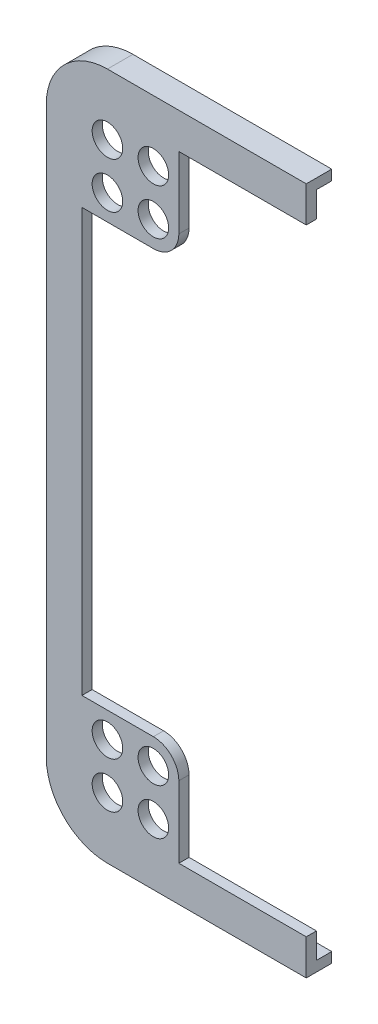
SolidWorks part; units mm, degrees
ref_plane "Front Plane" through (0, 0, 0) normal (0, 0, 1) x (1, 0, 0)
ref_plane "Top Plane" through (0, 0, 0) normal (0, 1, 0) x (1, 0, 0)
ref_plane "Right Plane" through (0, 0, 0) normal (1, 0, 0) x (0, 0, -1)
sketch "Sketch1" plane through (0, 0, 0) normal (0, 0, 1) x (1, 0, 0)
  line L0 (157.8919, 26.2701) -> (191.7747, 29.0915)
  line L1 (157.8919, 26.2701) -> (191.7747, 26.2701)
  line L2 (157.8919, 26.2701) -> (157.8919, 29.0915)
  line L3 (157.8919, 29.0915) -> (191.7747, 29.0915)
  line L4 (191.7747, 26.2701) -> (191.7747, 29.0915)
  line L5 (123.8919, 26.2701) -> (90.0092, 26.2701)
  line L6 (123.8919, 26.2701) -> (123.8919, 29.0915)
  line L7 (123.8919, 29.0915) -> (90.0092, 29.0915)
  line L8 (90.0092, 26.2701) -> (90.0092, 29.0915)
  line L9 (90.0092, 29.0915) -> (123.8919, 26.2701)
  line L10 (168.0919, 58.3601) -> (194.8735, 70.7292)
  line L11 (168.0919, 58.3601) -> (194.8735, 58.3601)
  line L12 (168.0919, 58.3601) -> (168.0919, 70.7292)
  line L13 (168.0919, 70.7292) -> (194.8735, 70.7292)
  line L14 (194.8735, 58.3601) -> (194.8735, 70.7292)
  line L15 (194.8735, 70.7292) -> (224.3587, 70.7292)
  line L16 (194.8735, 70.7292) -> (194.8735, 69.7923)
  line L17 (194.8735, 69.7923) -> (224.3587, 69.7923)
  line L18 (224.3587, 70.7292) -> (224.3587, 69.7923)
  line L19 (224.3587, 69.7923) -> (253.5106, 69.7923)
  line L20 (224.3587, 69.7923) -> (224.3587, 65.2742)
  line L21 (224.3587, 65.2742) -> (253.5106, 65.2742)
  line L22 (253.5106, 69.7923) -> (253.5106, 65.2742)
  line L23 (224.3587, 69.7923) -> (194.8735, 70.7292)
  line L24 (253.5106, 65.2742) -> (224.3587, 69.7923)
  line L25 (170.7502, 87.7401) -> (168.0919, 58.3601)
  line L26 (168.0919, 58.3601) -> (170.7502, 58.3601)
  line L27 (168.0919, 58.3601) -> (168.0919, 87.7401)
  line L28 (168.0919, 87.7401) -> (170.7502, 87.7401)
  line L29 (170.7502, 58.3601) -> (170.7502, 87.7401)
  line L30 (52.9966, 89.4705) -> (24.4119, 82.1791)
  line L31 (24.4119, 82.1791) -> (52.9966, 82.1791)
  line L32 (24.4119, 82.1791) -> (24.4119, 89.4705)
  line L33 (24.4119, 89.4705) -> (52.9966, 89.4705)
  line L34 (52.9966, 82.1791) -> (52.9966, 89.4705)
  line L35 (82.4966, 89.4705) -> (109.0019, 89.4705)
  line L36 (82.4966, 89.4705) -> (82.4966, 76.5201)
  line L37 (82.4966, 76.5201) -> (109.0019, 76.5201)
  line L38 (109.0019, 89.4705) -> (109.0019, 76.5201)
  line L39 (92.4554, 117.2387) -> (82.4966, 117.2387)
  line L40 (92.4554, 117.2387) -> (92.4554, 89.4705)
  line L41 (92.4554, 89.4705) -> (82.4966, 89.4705)
  line L42 (82.4966, 117.2387) -> (82.4966, 89.4705)
  line L43 (92.4554, 117.2387) -> (82.4966, 89.4705)
  line L44 (109.0019, 76.5201) -> (82.4966, 89.4705)
  circle A0 centre (123.8919, 26.2701) radius 14.25
  circle A1 centre (157.8919, 26.2701) radius 14.25
  circle A2 centre (90.0092, 29.0915) radius 14.25
  circle A3 centre (191.7747, 29.0915) radius 14.25
  circle A4 centre (82.4966, 89.4705) radius 11.25
  circle A5 centre (92.4554, 117.2387) radius 11.25
  circle A6 centre (52.9966, 89.4705) radius 11.25
  circle A7 centre (109.0019, 76.5201) radius 11.25
  circle A8 centre (24.4119, 82.1791) radius 11.25
  circle A9 centre (170.7502, 87.7401) radius 11.25
  circle A10 centre (168.0919, 58.3601) radius 11.25
  circle A11 centre (197.5318, 100.1092) radius 11.25
  circle A12 centre (194.8735, 70.7292) radius 11.25
  circle A13 centre (227.0169, 99.1723) radius 11.25
  circle A14 centre (224.3587, 69.7923) radius 11.25
  circle A15 centre (256.1689, 94.6541) radius 11.25
  circle A16 centre (253.5106, 65.2742) radius 11.25
  circle A17 centre (24.4119, 82.1791) radius 12
  circle A18 centre (52.9966, 89.4705) radius 12
  circle A19 centre (92.4554, 117.2387) radius 12
  circle A20 centre (82.4966, 89.4705) radius 12
  circle A21 centre (109.0019, 76.5201) radius 12
  circle A22 centre (168.0919, 58.3601) radius 12
  circle A23 centre (194.8735, 70.7292) radius 12
  circle A24 centre (224.3587, 69.7923) radius 12
  circle A25 centre (253.5106, 65.2742) radius 12
  circle A26 centre (256.1689, 94.6541) radius 12
  circle A27 centre (227.0169, 99.1723) radius 12
  circle A28 centre (197.5318, 100.1092) radius 12
  circle A29 centre (170.7502, 87.7401) radius 12
  circle A30 centre (191.7747, 29.0915) radius 15
  circle A31 centre (157.8919, 26.2701) radius 15
  circle A32 centre (123.8919, 26.2701) radius 15
  circle A33 centre (90.0092, 29.0915) radius 15
  circle A34 centre (173.429, 117.1182) radius 11.25
  circle A35 centre (173.429, 117.1182) radius 12
  dimension "D1" = 28.5
  dimension "D2" = 22.5
  dimension "D3" = 0.75
  dimension "D4" = 0.75
  dimension "D34" = 34
  dimension "D5" = 29.5
  dimension "D6" = 29.5
  dimension "D7" = 29.5
  dimension "D8" = 29.5
  dimension "D9" = 29.5
  dimension "D10" = 29.5
  dimension "D11" = 29.5
  dimension "D12" = 29.5
  dimension "D13" = 29.5
  dimension "D14" = 29.5
  dimension "D15" = 29.5
  dimension "D16" = 29.5
  dimension "D17" = 29.5
  dimension "D18" = 29.5
  dimension "D19" = 34
  dimension "D20" = 34
  dimension "D21" = 32.09
  dimension "D22" = 10.2
  dimension "D23" = 4.76
  dimension "D24" = 4.76
  dimension "D25" = 24.79
  dimension "D26" = 1.82
  dimension "D27" = 8.81
  dimension "D28" = 84.83
  dimension "D29" = 75.69
  dimension "D30" = 70.27
  dimension "D31" = 26.04
  dimension "D32" = 14.89
  dimension "D33" = 50.25
  dimension "D35" = 29.5
  dimension "D36" = 29.5
sketch "Sketch4" plane through (-30.2083, 20.075, 0) normal (0, 0, 1) x (0.9781, -0.2079, 0)
  line L0 (86.1706, 94.1917) -> (105.2206, 75.1417)
  line L1 (67.1206, 94.1917) -> (86.1706, 94.1917)
  line L2 (67.1206, 94.1917) -> (67.1206, 75.1417)
  line L3 (67.1206, 75.1417) -> (86.1706, 75.1417)
  line L4 (86.1706, 94.1917) -> (86.1706, 75.1417)
  line L5 (86.1706, 94.1917) -> (105.2206, 94.1917)
  line L6 (86.1706, 94.1917) -> (86.1706, 75.1417)
  line L7 (86.1706, 75.1417) -> (105.2206, 75.1417)
  line L8 (105.2206, 94.1917) -> (105.2206, 75.1417)
  line L9 (105.2206, 94.1917) -> (124.2706, 94.1917)
  line L10 (105.2206, 94.1917) -> (105.2206, 75.1417)
  line L11 (105.2206, 75.1417) -> (124.2706, 75.1417)
  line L12 (124.2706, 94.1917) -> (124.2706, 75.1417)
  line L13 (86.1706, 94.1917) -> (105.2206, 94.1917)
  line L14 (86.1706, 94.1917) -> (86.1706, 113.2417)
  line L15 (86.1706, 113.2417) -> (105.2206, 113.2417)
  line L16 (105.2206, 94.1917) -> (105.2206, 113.2417)
  line L17 (66.9585, 85.1784) -> (124.4326, 84.1551)
  point P14 (95.6956, 84.6667)
  point P15 (95.6956, 84.6667)
  dimension "D1" = 19.05
sketch "Sketch9" plane through (0, 0, 0) normal (0, 0, 1) x (1, 0, 0)
  line L1 (17.3619, 89.2291) -> (31.4619, 89.2291)
  line L2 (17.3619, 89.2291) -> (17.3619, 75.1291)
  line L3 (17.3619, 75.1291) -> (31.4619, 75.1291)
  line L4 (31.4619, 89.2291) -> (31.4619, 75.1291)
  line L5 (45.9466, 96.5205) -> (60.0466, 96.5205)
  line L6 (45.9466, 96.5205) -> (45.9466, 82.4205)
  line L7 (45.9466, 82.4205) -> (60.0466, 82.4205)
  line L8 (60.0466, 96.5205) -> (60.0466, 82.4205)
  line L9 (75.4466, 96.5205) -> (89.5466, 96.5205)
  line L10 (75.4466, 96.5205) -> (75.4466, 82.4205)
  line L11 (75.4466, 82.4205) -> (89.5466, 82.4205)
  line L12 (89.5466, 96.5205) -> (89.5466, 82.4205)
  line L13 (101.9519, 83.5701) -> (116.0519, 83.5701)
  line L14 (101.9519, 83.5701) -> (101.9519, 69.4701)
  line L15 (101.9519, 69.4701) -> (116.0519, 69.4701)
  line L16 (116.0519, 83.5701) -> (116.0519, 69.4701)
  line L17 (85.4054, 124.2887) -> (99.5054, 124.2887)
  line L18 (85.4054, 124.2887) -> (85.4054, 110.1887)
  line L19 (85.4054, 110.1887) -> (99.5054, 110.1887)
  line L20 (99.5054, 124.2887) -> (99.5054, 110.1887)
  line L21 (82.9592, 36.1415) -> (97.0592, 36.1415)
  line L22 (82.9592, 36.1415) -> (82.9592, 22.0415)
  line L23 (82.9592, 22.0415) -> (97.0592, 22.0415)
  line L24 (97.0592, 36.1415) -> (97.0592, 22.0415)
  line L25 (116.8419, 33.3201) -> (130.9419, 33.3201)
  line L26 (116.8419, 33.3201) -> (116.8419, 19.2201)
  line L27 (116.8419, 19.2201) -> (130.9419, 19.2201)
  line L28 (130.9419, 33.3201) -> (130.9419, 19.2201)
  line L29 (150.8419, 33.3201) -> (164.9419, 33.3201)
  line L30 (150.8419, 33.3201) -> (150.8419, 19.2201)
  line L31 (150.8419, 19.2201) -> (164.9419, 19.2201)
  line L32 (164.9419, 33.3201) -> (164.9419, 19.2201)
  line L33 (184.7247, 36.1415) -> (198.8247, 36.1415)
  line L34 (184.7247, 36.1415) -> (184.7247, 22.0415)
  line L35 (184.7247, 22.0415) -> (198.8247, 22.0415)
  line L36 (198.8247, 36.1415) -> (198.8247, 22.0415)
  line L37 (260.5606, 58.2242) -> (246.4606, 58.2242)
  line L38 (260.5606, 58.2242) -> (260.5606, 72.3242)
  line L39 (260.5606, 72.3242) -> (246.4606, 72.3242)
  line L40 (246.4606, 58.2242) -> (246.4606, 72.3242)
  line L41 (217.3087, 76.8423) -> (231.4087, 76.8423)
  line L42 (217.3087, 76.8423) -> (217.3087, 62.7423)
  line L43 (217.3087, 62.7423) -> (231.4087, 62.7423)
  line L44 (231.4087, 76.8423) -> (231.4087, 62.7423)
  line L45 (187.8235, 77.7792) -> (201.9235, 77.7792)
  line L46 (187.8235, 77.7792) -> (187.8235, 63.6792)
  line L47 (187.8235, 63.6792) -> (201.9235, 63.6792)
  line L48 (201.9235, 77.7792) -> (201.9235, 63.6792)
  line L49 (161.0419, 65.4101) -> (175.1419, 65.4101)
  line L50 (161.0419, 65.4101) -> (161.0419, 51.3101)
  line L51 (161.0419, 51.3101) -> (175.1419, 51.3101)
  line L52 (175.1419, 65.4101) -> (175.1419, 51.3101)
  line L53 (163.7002, 94.7901) -> (177.8002, 94.7901)
  line L54 (163.7002, 94.7901) -> (163.7002, 80.6901)
  line L55 (163.7002, 80.6901) -> (177.8002, 80.6901)
  line L56 (177.8002, 94.7901) -> (177.8002, 80.6901)
  line L57 (190.4818, 107.1592) -> (204.5818, 107.1592)
  line L58 (190.4818, 107.1592) -> (190.4818, 93.0592)
  line L59 (190.4818, 93.0592) -> (204.5818, 93.0592)
  line L60 (204.5818, 107.1592) -> (204.5818, 93.0592)
  line L61 (219.9669, 106.2223) -> (234.0669, 106.2223)
  line L62 (219.9669, 106.2223) -> (219.9669, 92.1223)
  line L63 (219.9669, 92.1223) -> (234.0669, 92.1223)
  line L64 (234.0669, 106.2223) -> (234.0669, 92.1223)
  line L65 (249.1189, 101.7041) -> (263.2189, 101.7041)
  line L66 (249.1189, 101.7041) -> (249.1189, 87.6041)
  line L67 (249.1189, 87.6041) -> (263.2189, 87.6041)
  line L68 (263.2189, 101.7041) -> (263.2189, 87.6041)
  line L69 (166.379, 124.1682) -> (180.479, 124.1682)
  line L70 (166.379, 124.1682) -> (166.379, 110.0682)
  line L71 (166.379, 110.0682) -> (180.479, 110.0682)
  line L72 (180.479, 124.1682) -> (180.479, 110.0682)
  point P72 (24.4119, 89.2291)
  point P74 (52.9966, 96.5205)
  point P76 (82.4966, 96.5205)
  point P78 (92.4554, 124.2887)
  point P80 (109.0019, 83.5701)
  point P82 (90.0092, 36.1415)
  point P84 (123.8919, 33.3201)
  point P86 (157.8919, 33.3201)
  point P88 (191.7747, 36.1415)
  point P90 (168.0919, 65.4101)
  point P92 (170.7502, 94.7901)
  point P94 (173.429, 124.1682)
  point P96 (197.5318, 107.1592)
  point P98 (227.0169, 106.2223)
  point P100 (256.1689, 101.7041)
  point P102 (194.8735, 77.7792)
  point P104 (224.3587, 76.8423)
  point P106 (253.5106, 72.3242)
  point P108 (17.3619, 82.1791)
  point P109 (45.9466, 89.4705)
  point P110 (75.4466, 89.4705)
  point P111 (101.9519, 76.5201)
  point P112 (85.4054, 117.2387)
  point P113 (82.9592, 29.0915)
  point P114 (116.8419, 26.2701)
  point P115 (150.8419, 26.2701)
  point P116 (184.7247, 29.0915)
  point P118 (161.0419, 58.3601)
  point P119 (187.8235, 70.7292)
  point P120 (217.3087, 69.7923)
  point P121 (246.4606, 65.2742)
  point P122 (163.7002, 87.7401)
  point P123 (190.4818, 100.1092)
  point P124 (219.9669, 99.1723)
  point P125 (249.1189, 94.6541)
  point P126 (166.379, 117.1182)
  dimension "D1" = 14.1
sketch "Sketch10" plane through (-22.0981, 19.3454, 0) normal (0, 0, 1) x (0.9781, -0.2079, 0)
  line L1 (61.5108, 90.7441) -> (75.6108, 90.7441)
  line L2 (61.5108, 90.7441) -> (61.5108, 76.6441)
  line L3 (61.5108, 76.6441) -> (75.6108, 76.6441)
  line L4 (75.6108, 90.7441) -> (75.6108, 76.6441)
  line L5 (80.5608, 90.7441) -> (94.6608, 90.7441)
  line L6 (80.5608, 90.7441) -> (80.5608, 76.6441)
  line L7 (80.5608, 76.6441) -> (94.6608, 76.6441)
  line L8 (94.6608, 90.7441) -> (94.6608, 76.6441)
  line L9 (99.6108, 90.7441) -> (113.7108, 90.7441)
  line L10 (99.6108, 90.7441) -> (99.6108, 76.6441)
  line L11 (99.6108, 76.6441) -> (113.7108, 76.6441)
  line L12 (113.7108, 90.7441) -> (113.7108, 76.6441)
  line L13 (80.5608, 109.7941) -> (94.6608, 109.7941)
  line L14 (80.5608, 109.7941) -> (80.5608, 95.6941)
  line L15 (80.5608, 95.6941) -> (94.6608, 95.6941)
  line L16 (94.6608, 109.7941) -> (94.6608, 95.6941)
  line L17 (50.5121, 89.6359) -> (53.4436, 75.8441) construction
  line L18 (59.0358, 93.2191) -> (78.0858, 93.2191) construction
  line L19 (78.0858, 112.2691) -> (97.1358, 112.2691) construction
  line L20 (97.1358, 93.2191) -> (116.1858, 93.2191) construction
  line L21 (78.0858, 93.2191) -> (78.0858, 112.2691) construction
  line L23 (59.0358, 93.2191) -> (59.0358, 74.1691) construction
  point P16 (75.6108, 83.6941)
  point P17 (94.6608, 83.6941)
  point P18 (113.7108, 83.6941)
  point P19 (87.6108, 90.7441)
  point P20 (87.6108, 109.7941)
  point P23 (68.5608, 90.7441)
  point P26 (68.5608, 93.2191)
  point P29 (87.6108, 112.2691)
  point P30 (106.6608, 90.7441)
  point P33 (106.6608, 93.2191)
  point P34 (80.5608, 102.7441)
  point P37 (78.0858, 102.7441)
  point P42 (59.0358, 83.6941)
  point P43 (61.5108, 83.6941)
sketch "Sketch14" plane through (0, 0, 0) normal (0, 0, 1) x (1, 0, 0)
  line L0 (165.1144, 80.6901) -> (163.7002, 82.1043)
  line L1 (163.7002, 93.3758) -> (165.1144, 94.7901)
  line L2 (177.8002, 93.3758) -> (176.386, 94.7901)
  line L3 (179.0648, 110.0682) -> (180.479, 111.4824)
  line L4 (166.379, 111.4824) -> (167.7932, 110.0682)
  line L5 (166.379, 122.754) -> (167.7932, 124.1682)
  line L6 (179.0648, 124.1682) -> (180.479, 122.754)
  line L7 (203.1676, 93.0592) -> (204.5818, 94.4734)
  line L8 (17.3619, 89.2291) -> (17.3619, 75.1291) construction
  line L9 (17.3619, 89.2291) -> (31.4619, 89.2291) construction
  line L10 (17.3619, 87.8149) -> (18.7761, 89.2291)
  line L11 (17.3619, 75.1291) -> (31.4619, 75.1291) construction
  line L12 (31.4619, 89.2291) -> (31.4619, 75.1291) construction
  line L13 (45.9466, 96.5205) -> (60.0466, 96.5205) construction
  line L14 (60.0466, 96.5205) -> (60.0466, 82.4205) construction
  line L15 (45.9466, 96.5205) -> (45.9466, 82.4205) construction
  line L16 (45.9466, 82.4205) -> (60.0466, 82.4205) construction
  line L17 (85.4054, 124.2887) -> (85.4054, 110.1887) construction
  line L18 (85.4054, 124.2887) -> (99.5054, 124.2887) construction
  line L19 (99.5054, 124.2887) -> (99.5054, 110.1887) construction
  line L20 (85.4054, 110.1887) -> (99.5054, 110.1887) construction
  line L21 (101.9519, 83.5701) -> (101.9519, 69.4701) construction
  line L22 (101.9519, 83.5701) -> (116.0519, 83.5701) construction
  line L23 (116.0519, 83.5701) -> (116.0519, 69.4701) construction
  line L24 (101.9519, 69.4701) -> (116.0519, 69.4701) construction
  line L25 (91.2712, 73.6044) -> (105.0631, 70.6729) construction
  line L26 (107.9947, 84.4647) -> (105.0631, 70.6729) construction
  line L27 (94.2028, 87.3963) -> (107.9947, 84.4647) construction
  line L28 (94.2028, 87.3963) -> (91.2712, 73.6044) construction
  line L29 (72.6375, 77.5651) -> (86.4294, 74.6336) construction
  line L30 (89.361, 88.4255) -> (86.4294, 74.6336) construction
  line L31 (75.5691, 91.357) -> (89.361, 88.4255) construction
  line L32 (75.5691, 91.357) -> (72.6375, 77.5651) construction
  line L33 (56.9354, 95.3177) -> (54.0038, 81.5259) construction
  line L34 (56.9354, 95.3177) -> (70.7273, 92.3862) construction
  line L35 (70.7273, 92.3862) -> (67.7957, 78.5943) construction
  line L36 (54.0038, 81.5259) -> (67.7957, 78.5943) construction
  line L37 (76.5983, 96.1988) -> (90.3901, 93.2673) construction
  line L38 (93.3217, 107.0592) -> (90.3901, 93.2673) construction
  line L39 (79.5298, 109.9907) -> (76.5983, 96.1988) construction
  line L40 (79.5298, 109.9907) -> (93.3217, 107.0592) construction
  line L41 (82.9592, 36.1415) -> (82.9592, 22.0415) construction
  line L42 (82.9592, 36.1415) -> (97.0592, 36.1415) construction
  line L43 (82.9592, 22.0415) -> (97.0592, 22.0415) construction
  line L44 (97.0592, 36.1415) -> (97.0592, 22.0415) construction
  line L45 (116.8419, 33.3201) -> (116.8419, 19.2201) construction
  line L46 (116.8419, 33.3201) -> (130.9419, 33.3201) construction
  line L47 (116.8419, 19.2201) -> (130.9419, 19.2201) construction
  line L48 (130.9419, 33.3201) -> (130.9419, 19.2201) construction
  line L49 (150.8419, 33.3201) -> (150.8419, 19.2201) construction
  line L50 (150.8419, 33.3201) -> (164.9419, 33.3201) construction
  line L51 (164.9419, 33.3201) -> (164.9419, 19.2201) construction
  line L52 (150.8419, 19.2201) -> (164.9419, 19.2201) construction
  line L53 (184.7247, 36.1415) -> (184.7247, 22.0415) construction
  line L54 (184.7247, 22.0415) -> (198.8247, 22.0415) construction
  line L55 (198.8247, 36.1415) -> (198.8247, 22.0415) construction
  line L56 (184.7247, 36.1415) -> (198.8247, 36.1415) construction
  line L57 (161.0419, 65.4101) -> (175.1419, 65.4101) construction
  line L58 (175.1419, 65.4101) -> (175.1419, 51.3101) construction
  line L59 (161.0419, 51.3101) -> (175.1419, 51.3101) construction
  line L60 (161.0419, 65.4101) -> (161.0419, 51.3101) construction
  line L61 (187.8235, 77.7792) -> (187.8235, 63.6792) construction
  line L62 (187.8235, 77.7792) -> (201.9235, 77.7792) construction
  line L63 (187.8235, 63.6792) -> (201.9235, 63.6792) construction
  line L64 (201.9235, 77.7792) -> (201.9235, 63.6792) construction
  line L65 (217.3087, 76.8423) -> (217.3087, 62.7423) construction
  line L66 (217.3087, 76.8423) -> (231.4087, 76.8423) construction
  line L67 (231.4087, 76.8423) -> (231.4087, 62.7423) construction
  line L68 (217.3087, 62.7423) -> (231.4087, 62.7423) construction
  line L69 (260.5606, 58.2242) -> (246.4606, 58.2242) construction
  line L70 (260.5606, 58.2242) -> (260.5606, 72.3242) construction
  line L71 (246.4606, 58.2242) -> (246.4606, 72.3242) construction
  line L72 (260.5606, 72.3242) -> (246.4606, 72.3242) construction
  line L73 (249.1189, 101.7041) -> (263.2189, 101.7041) construction
  line L74 (263.2189, 101.7041) -> (263.2189, 87.6041) construction
  line L75 (249.1189, 87.6041) -> (263.2189, 87.6041) construction
  line L76 (249.1189, 101.7041) -> (249.1189, 87.6041) construction
  line L77 (219.9669, 106.2223) -> (219.9669, 92.1223) construction
  line L78 (219.9669, 106.2223) -> (234.0669, 106.2223) construction
  line L79 (234.0669, 106.2223) -> (234.0669, 92.1223) construction
  line L80 (219.9669, 92.1223) -> (234.0669, 92.1223) construction
  line L81 (190.4818, 107.1592) -> (204.5818, 107.1592) construction
  line L82 (204.5818, 107.1592) -> (204.5818, 93.0592) construction
  line L83 (190.4818, 93.0592) -> (204.5818, 93.0592) construction
  line L84 (190.4818, 107.1592) -> (190.4818, 93.0592) construction
  line L85 (163.7002, 94.7901) -> (177.8002, 94.7901) construction
  line L86 (177.8002, 94.7901) -> (177.8002, 80.6901) construction
  line L87 (163.7002, 80.6901) -> (177.8002, 80.6901) construction
  line L88 (163.7002, 94.7901) -> (163.7002, 80.6901) construction
  line L89 (180.479, 124.1682) -> (180.479, 110.0682) construction
  line L90 (166.379, 110.0682) -> (180.479, 110.0682) construction
  line L91 (166.379, 124.1682) -> (166.379, 110.0682) construction
  line L92 (166.379, 124.1682) -> (180.479, 124.1682) construction
  line L93 (17.3619, 76.5433) -> (18.7761, 75.1291)
  line L94 (30.0477, 75.1291) -> (31.4619, 76.5433)
  line L95 (31.4619, 87.8149) -> (30.0477, 89.2291)
  line L96 (45.9466, 95.1063) -> (47.3608, 96.5205)
  line L97 (45.9466, 83.8347) -> (47.3608, 82.4205)
  line L98 (54.2979, 82.9092) -> (55.3871, 81.2318)
  line L99 (58.6323, 82.4205) -> (60.0466, 83.8347)
  line L100 (56.6413, 93.9344) -> (58.3187, 95.0237)
  line L101 (58.6323, 96.5205) -> (60.0466, 95.1063)
  line L102 (69.3439, 92.6802) -> (70.4332, 91.0029)
  line L103 (68.0897, 79.9776) -> (66.4124, 78.8883)
  line L104 (75.2751, 89.9737) -> (76.9524, 91.063)
  line L105 (72.9316, 78.9484) -> (74.0208, 77.2711)
  line L106 (85.0461, 74.9276) -> (86.7234, 76.0169)
  line L107 (89.0669, 87.0421) -> (87.9777, 88.7195)
  line L108 (89.0068, 93.5613) -> (90.6842, 94.6506)
  line L109 (76.8923, 97.5822) -> (77.9816, 95.9048)
  line L110 (91.9384, 107.3532) -> (93.0277, 105.6759)
  line L111 (79.2358, 108.6074) -> (80.9131, 109.6967)
  line L112 (85.4054, 111.6029) -> (86.8196, 110.1887)
  line L113 (98.0912, 110.1887) -> (99.5054, 111.6029)
  line L114 (98.0912, 124.2887) -> (99.5054, 122.8745)
  line L115 (85.4054, 122.8745) -> (86.8196, 124.2887)
  line L116 (93.9088, 86.013) -> (95.5861, 87.1023)
  line L117 (91.5653, 74.9877) -> (92.6546, 73.3104)
  line L118 (103.6798, 70.9669) -> (105.3572, 72.0562)
  line L119 (106.6114, 84.7588) -> (107.7006, 83.0814)
  line L120 (101.9519, 82.1559) -> (103.3662, 83.5701)
  line L121 (101.9519, 70.8843) -> (103.3662, 69.4701)
  line L122 (114.6377, 69.4701) -> (116.0519, 70.8843)
  line L123 (116.0519, 82.1559) -> (114.6377, 83.5701)
  line L124 (82.9592, 34.7272) -> (84.3734, 36.1415)
  line L125 (82.9592, 23.4557) -> (84.3734, 22.0415)
  line L126 (95.645, 22.0415) -> (97.0592, 23.4557)
  line L127 (97.0592, 34.7272) -> (95.645, 36.1415)
  line L128 (116.8419, 31.9059) -> (118.2562, 33.3201)
  line L129 (116.8419, 20.6343) -> (118.2562, 19.2201)
  line L130 (129.5277, 19.2201) -> (130.9419, 20.6343)
  line L131 (130.9419, 31.9059) -> (129.5277, 33.3201)
  line L132 (150.8419, 31.9059) -> (152.2562, 33.3201)
  line L133 (150.8419, 20.6343) -> (152.2562, 19.2201)
  line L134 (163.5277, 19.2201) -> (164.9419, 20.6343)
  line L135 (164.9419, 31.9059) -> (163.5277, 33.3201)
  line L136 (184.7247, 34.7272) -> (186.1389, 36.1415)
  line L137 (184.7247, 23.4557) -> (186.1389, 22.0415)
  line L138 (197.4105, 22.0415) -> (198.8247, 23.4557)
  line L139 (198.8247, 34.7272) -> (197.4105, 36.1415)
  line L140 (173.7277, 51.3101) -> (175.1419, 52.7243)
  line L141 (161.0419, 52.7243) -> (162.4562, 51.3101)
  line L142 (161.0419, 63.9959) -> (162.4562, 65.4101)
  line L143 (173.7277, 65.4101) -> (175.1419, 63.9959)
  line L144 (187.8235, 65.0934) -> (189.2378, 63.6792)
  line L145 (200.5093, 63.6792) -> (201.9235, 65.0934)
  line L146 (200.5093, 77.7792) -> (201.9235, 76.365)
  line L147 (187.8235, 76.365) -> (189.2378, 77.7792)
  line L148 (176.386, 80.6901) -> (177.8002, 82.1043)
  line L149 (204.5818, 105.745) -> (203.1676, 107.1592)
  line L150 (191.896, 107.1592) -> (190.4818, 105.745)
  line L151 (190.4818, 94.4734) -> (191.896, 93.0592)
  line L152 (219.9669, 104.8081) -> (221.3812, 106.2223)
  line L153 (232.6527, 106.2223) -> (234.0669, 104.8081)
  line L154 (234.0669, 93.5365) -> (232.6527, 92.1223)
  line L155 (219.9669, 93.5365) -> (221.3812, 92.1223)
  line L156 (229.9944, 76.8423) -> (231.4087, 75.4281)
  line L157 (217.3087, 75.4281) -> (218.7229, 76.8423)
  line L158 (217.3087, 64.1565) -> (218.7229, 62.7423)
  line L159 (229.9944, 62.7423) -> (231.4087, 64.1565)
  line L160 (259.1464, 72.3242) -> (260.5606, 70.9099)
  line L161 (246.4606, 70.9099) -> (247.8748, 72.3242)
  line L162 (259.1464, 58.2242) -> (260.5606, 59.6384)
  line L163 (247.8748, 58.2242) -> (246.4606, 59.6384)
  line L164 (261.8047, 87.6041) -> (263.2189, 89.0183)
  line L165 (249.1189, 89.0183) -> (250.5331, 87.6041)
  line L166 (249.1189, 100.2899) -> (250.5331, 101.7041)
  line L167 (261.8047, 101.7041) -> (263.2189, 100.2899)
  line L168 (75.4466, 96.5205) -> (75.4466, 82.4205) construction
  line L169 (75.4466, 96.5205) -> (89.5466, 96.5205) construction
  line L170 (89.5466, 96.5205) -> (89.5466, 82.4205) construction
  line L171 (75.4466, 82.4205) -> (89.5466, 82.4205) construction
  line L172 (76.8608, 96.5205) -> (75.4466, 95.1063)
  line L173 (88.1323, 96.5205) -> (89.5466, 95.1063)
  line L174 (89.5466, 83.8347) -> (88.1323, 82.4205)
  line L175 (75.4466, 83.8347) -> (76.8608, 82.4205)
  arc A0 (17.3619, 87.8149) -> (18.7761, 89.2291) centre (18.069, 88.522) cw
  arc A1 (18.7761, 75.1291) -> (17.3619, 76.5433) centre (18.069, 75.8362) cw
  arc A2 (31.4619, 76.5433) -> (30.0477, 75.1291) centre (30.7548, 75.8362) cw
  arc A3 (30.0477, 89.2291) -> (31.4619, 87.8149) centre (30.7548, 88.522) cw
  arc A4 (58.6323, 96.5205) -> (60.0466, 95.1063) centre (59.3394, 95.8134) cw
  arc A5 (45.9466, 95.1063) -> (47.3608, 96.5205) centre (46.6537, 95.8134) cw
  arc A6 (47.3608, 82.4205) -> (45.9466, 83.8347) centre (46.6537, 83.1276) cw
  arc A7 (60.0466, 83.8347) -> (58.6323, 82.4205) centre (59.3394, 83.1276) cw
  arc A8 (85.4054, 122.8745) -> (86.8196, 124.2887) centre (86.1125, 123.5816) cw
  arc A9 (98.0912, 124.2887) -> (99.5054, 122.8745) centre (98.7983, 123.5816) cw
  arc A10 (99.5054, 111.6029) -> (98.0912, 110.1887) centre (98.7983, 110.8958) cw
  arc A11 (85.4054, 111.6029) -> (86.8196, 110.1887) centre (86.1125, 110.8958) ccw
  arc A12 (101.9519, 82.1559) -> (103.3662, 83.5701) centre (102.6591, 82.863) cw
  arc A13 (114.6377, 83.5701) -> (116.0519, 82.1559) centre (115.3448, 82.863) cw
  arc A14 (116.0519, 70.8843) -> (114.6377, 69.4701) centre (115.3448, 70.1772) cw
  arc A15 (101.9519, 70.8843) -> (103.3662, 69.4701) centre (102.6591, 70.1772) ccw
  arc A16 (103.6798, 70.9669) -> (105.3572, 72.0562) centre (104.5185, 71.5115) ccw
  arc A17 (106.6114, 84.7588) -> (107.7006, 83.0814) centre (107.156, 83.9201) cw
  arc A18 (93.9088, 86.013) -> (95.5861, 87.1023) centre (94.7474, 86.5576) cw
  arc A19 (91.5653, 74.9877) -> (92.6546, 73.3104) centre (92.1099, 74.1491) ccw
  arc A20 (85.0461, 74.9276) -> (86.7234, 76.0169) centre (85.8848, 75.4722) ccw
  arc A21 (87.9777, 88.7195) -> (89.0669, 87.0421) centre (88.5223, 87.8808) cw
  arc A22 (75.2751, 89.9737) -> (76.9524, 91.063) centre (76.1137, 90.5183) cw
  arc A23 (72.9316, 78.9484) -> (74.0208, 77.2711) centre (73.4762, 78.1098) ccw
  arc A24 (56.6413, 93.9344) -> (58.3187, 95.0237) centre (57.48, 94.4791) cw
  arc A25 (69.3439, 92.6802) -> (70.4332, 91.0029) centre (69.8886, 91.8415) cw
  arc A26 (68.0897, 79.9776) -> (66.4124, 78.8883) centre (67.2511, 79.433) cw
  arc A27 (54.2979, 82.9092) -> (55.3871, 81.2318) centre (54.8425, 82.0705) ccw
  arc A28 (89.0068, 93.5613) -> (90.6842, 94.6506) centre (89.8455, 94.106) ccw
  arc A29 (76.8923, 97.5822) -> (77.9816, 95.9048) centre (77.4369, 96.7435) ccw
  arc A30 (79.2358, 108.6074) -> (80.9131, 109.6967) centre (80.0744, 109.1521) cw
  arc A31 (91.9384, 107.3532) -> (93.0277, 105.6759) centre (92.483, 106.5145) cw
  arc A32 (82.9592, 34.7272) -> (84.3734, 36.1415) centre (83.6663, 35.4344) cw
  arc A33 (82.9592, 23.4557) -> (84.3734, 22.0415) centre (83.6663, 22.7486) ccw
  arc A34 (95.645, 22.0415) -> (97.0592, 23.4557) centre (96.3521, 22.7486) ccw
  arc A35 (95.645, 36.1415) -> (97.0592, 34.7272) centre (96.3521, 35.4344) cw
  arc A36 (116.8419, 31.9059) -> (118.2562, 33.3201) centre (117.5491, 32.613) cw
  arc A37 (116.8419, 20.6343) -> (118.2562, 19.2201) centre (117.5491, 19.9272) ccw
  arc A38 (129.5277, 19.2201) -> (130.9419, 20.6343) centre (130.2348, 19.9272) ccw
  arc A39 (129.5277, 33.3201) -> (130.9419, 31.9059) centre (130.2348, 32.613) cw
  arc A40 (150.8419, 31.9059) -> (152.2562, 33.3201) centre (151.5491, 32.613) cw
  arc A41 (163.5277, 33.3201) -> (164.9419, 31.9059) centre (164.2348, 32.613) cw
  arc A42 (164.9419, 20.6343) -> (163.5277, 19.2201) centre (164.2348, 19.9272) cw
  arc A43 (150.8419, 20.6343) -> (152.2562, 19.2201) centre (151.5491, 19.9272) ccw
  arc A44 (184.7247, 23.4557) -> (186.1389, 22.0415) centre (185.4318, 22.7486) ccw
  arc A45 (197.4105, 22.0415) -> (198.8247, 23.4557) centre (198.1176, 22.7486) ccw
  arc A46 (197.4105, 36.1415) -> (198.8247, 34.7272) centre (198.1176, 35.4344) cw
  arc A47 (184.7247, 34.7272) -> (186.1389, 36.1415) centre (185.4318, 35.4344) cw
  arc A48 (173.7277, 65.4101) -> (175.1419, 63.9959) centre (174.4348, 64.703) cw
  arc A49 (175.1419, 52.7243) -> (173.7277, 51.3101) centre (174.4348, 52.0172) cw
  arc A50 (161.0419, 52.7243) -> (162.4562, 51.3101) centre (161.7491, 52.0172) ccw
  arc A51 (161.0419, 63.9959) -> (162.4562, 65.4101) centre (161.7491, 64.703) cw
  arc A52 (187.8235, 76.365) -> (189.2378, 77.7792) centre (188.5306, 77.0721) cw
  arc A53 (187.8235, 65.0934) -> (189.2378, 63.6792) centre (188.5306, 64.3863) ccw
  arc A54 (200.5093, 63.6792) -> (201.9235, 65.0934) centre (201.2164, 64.3863) ccw
  arc A55 (200.5093, 77.7792) -> (201.9235, 76.365) centre (201.2164, 77.0721) cw
  arc A56 (217.3087, 75.4281) -> (218.7229, 76.8423) centre (218.0158, 76.1352) cw
  arc A57 (229.9944, 76.8423) -> (231.4087, 75.4281) centre (230.7016, 76.1352) cw
  arc A58 (231.4087, 64.1565) -> (229.9944, 62.7423) centre (230.7016, 63.4494) cw
  arc A59 (217.3087, 64.1565) -> (218.7229, 62.7423) centre (218.0158, 63.4494) ccw
  arc A60 (259.1464, 58.2242) -> (260.5606, 59.6384) centre (259.8535, 58.9313) ccw
  arc A61 (246.4606, 59.6384) -> (247.8748, 58.2242) centre (247.1677, 58.9313) ccw
  arc A62 (246.4606, 70.9099) -> (247.8748, 72.3242) centre (247.1677, 71.617) cw
  arc A63 (259.1464, 72.3242) -> (260.5606, 70.9099) centre (259.8535, 71.617) cw
  arc A64 (261.8047, 101.7041) -> (263.2189, 100.2899) centre (262.5118, 100.997) cw
  arc A65 (263.2189, 89.0183) -> (261.8047, 87.6041) centre (262.5118, 88.3112) cw
  arc A66 (250.5331, 87.6041) -> (249.1189, 89.0183) centre (249.826, 88.3112) cw
  arc A67 (249.1189, 100.2899) -> (250.5331, 101.7041) centre (249.826, 100.997) cw
  arc A68 (219.9669, 104.8081) -> (221.3812, 106.2223) centre (220.674, 105.5152) cw
  arc A69 (232.6527, 106.2223) -> (234.0669, 104.8081) centre (233.3598, 105.5152) cw
  arc A70 (234.0669, 93.5365) -> (232.6527, 92.1223) centre (233.3598, 92.8294) cw
  arc A71 (221.3812, 92.1223) -> (219.9669, 93.5365) centre (220.674, 92.8294) cw
  arc A72 (203.1676, 107.1592) -> (204.5818, 105.745) centre (203.8747, 106.4521) cw
  arc A73 (204.5818, 94.4734) -> (203.1676, 93.0592) centre (203.8747, 93.7663) cw
  arc A74 (191.896, 93.0592) -> (190.4818, 94.4734) centre (191.1889, 93.7663) cw
  arc A75 (190.4818, 105.745) -> (191.896, 107.1592) centre (191.1889, 106.4521) cw
  arc A76 (176.386, 94.7901) -> (177.8002, 93.3758) centre (177.0931, 94.0829) cw
  arc A77 (177.8002, 82.1043) -> (176.386, 80.6901) centre (177.0931, 81.3972) cw
  arc A78 (165.1144, 80.6901) -> (163.7002, 82.1043) centre (164.4073, 81.3972) cw
  arc A79 (163.7002, 93.3758) -> (165.1144, 94.7901) centre (164.4073, 94.0829) cw
  arc A80 (180.479, 111.4824) -> (179.0648, 110.0682) centre (179.7719, 110.7753) cw
  arc A81 (167.7932, 110.0682) -> (166.379, 111.4824) centre (167.0861, 110.7753) cw
  arc A82 (179.0648, 124.1682) -> (180.479, 122.754) centre (179.7719, 123.4611) cw
  arc A83 (166.379, 122.754) -> (167.7932, 124.1682) centre (167.0861, 123.4611) cw
  arc A84 (75.4466, 95.1063) -> (76.8608, 96.5205) centre (76.1537, 95.8134) cw
  arc A85 (88.1323, 96.5205) -> (89.5466, 95.1063) centre (88.8394, 95.8134) cw
  arc A86 (89.5466, 83.8347) -> (88.1323, 82.4205) centre (88.8394, 83.1276) cw
  arc A87 (76.8608, 82.4205) -> (75.4466, 83.8347) centre (76.1537, 83.1276) cw
  dimension "D1" = 45
  dimension "D2" = 1
  dimension "D71" = 45
  dimension "D3" = 45
  dimension "D4" = 45
  dimension "D5" = 45
  dimension "D6" = 45
  dimension "D7" = 45
  dimension "D8" = 45
  dimension "D9" = 45
  dimension "D10" = 45
  dimension "D11" = 45
  dimension "D12" = 45
  dimension "D13" = 45
  dimension "D14" = 45
  dimension "D15" = 45
  dimension "D16" = 45
  dimension "D17" = 45
  dimension "D18" = 45
  dimension "D19" = 45
  dimension "D20" = 45
  dimension "D21" = 45
  dimension "D22" = 45
  dimension "D23" = 45
  dimension "D24" = 45
  dimension "D25" = 45
  dimension "D26" = 45
  dimension "D27" = 45
  dimension "D28" = 45
  dimension "D29" = 45
  dimension "D30" = 45
  dimension "D31" = 45
  dimension "D32" = 45
  dimension "D33" = 45
  dimension "D34" = 45
  dimension "D35" = 45
  dimension "D36" = 45
  dimension "D37" = 45
  dimension "D38" = 45
  dimension "D39" = 45
  dimension "D40" = 45
  dimension "D41" = 45
  dimension "D42" = 45
  dimension "D43" = 45
  dimension "D44" = 45
  dimension "D45" = 45
  dimension "D46" = 45
  dimension "D47" = 45
  dimension "D48" = 45
  dimension "D49" = 45
  dimension "D50" = 45
  dimension "D51" = 45
  dimension "D52" = 45
  dimension "D53" = 45
  dimension "D54" = 45
  dimension "D55" = 45
  dimension "D56" = 45
  dimension "D57" = 45
  dimension "D58" = 45
  dimension "D59" = 45
  dimension "D60" = 45
  dimension "D61" = 45
  dimension "D62" = 45
  dimension "D63" = 45
  dimension "D64" = 45
  dimension "D65" = 45
  dimension "D66" = 45
  dimension "D67" = 45
  dimension "D68" = 45
  dimension "D69" = 45
  dimension "D70" = 45
  dimension "D72" = 45
  dimension "D73" = 45
  dimension "D74" = 45
  dimension "D75" = 45
  dimension "D76" = 45
  dimension "D77" = 45
  dimension "D78" = 45
  dimension "D79" = 45
  dimension "D80" = 45
  dimension "D81" = 45
  dimension "D82" = 45
  dimension "D83" = 45
  dimension "D84" = 45
  dimension "D85" = 45
  dimension "D86" = 45
  dimension "D87" = 45
  dimension "D88" = 45
  dimension "D89" = 45
sketch "Sketch16" plane through (0, 0, 0) normal (0, 0, 1) x (1, 0, 0)
  line L0 (81.0092, 30.6915) -> (99.0092, 30.6915)
  line L5 (17.3619, 89.2291) -> (17.3619, 75.1291) construction
  line L6 (81.0092, 30.6915) -> (81.0092, 27.4915)
  line L7 (17.3619, 75.1291) -> (31.4619, 75.1291) construction
  line L8 (15.4119, 83.7791) -> (33.4119, 83.7791)
  line L9 (15.4119, 83.7791) -> (15.4119, 80.5791)
  line L10 (15.4119, 80.5791) -> (33.4119, 80.5791)
  line L11 (33.4119, 83.7791) -> (33.4119, 80.5791)
  line L12 (81.0092, 27.4915) -> (99.0092, 27.4915)
  line L13 (99.0092, 30.6915) -> (99.0092, 27.4915)
  line L14 (114.8919, 27.8701) -> (132.8919, 27.8701)
  line L15 (114.8919, 27.8701) -> (114.8919, 24.6701)
  line L16 (114.8919, 24.6701) -> (132.8919, 24.6701)
  line L17 (132.8919, 27.8701) -> (132.8919, 24.6701)
  line L18 (148.8919, 27.8701) -> (166.8919, 27.8701)
  line L19 (148.8919, 27.8701) -> (148.8919, 24.6701)
  line L20 (148.8919, 24.6701) -> (166.8919, 24.6701)
  line L21 (166.8919, 27.8701) -> (166.8919, 24.6701)
  line L22 (182.7747, 30.6915) -> (200.7747, 30.6915)
  line L23 (182.7747, 30.6915) -> (182.7747, 27.4915)
  line L24 (182.7747, 27.4915) -> (200.7747, 27.4915)
  line L25 (200.7747, 30.6915) -> (200.7747, 27.4915)
  line L26 (43.9966, 91.0705) -> (61.9966, 91.0705)
  line L27 (43.9966, 91.0705) -> (43.9966, 87.8705)
  line L28 (43.9966, 87.8705) -> (61.9966, 87.8705)
  line L29 (61.9966, 91.0705) -> (61.9966, 87.8705)
  line L30 (73.4966, 91.0705) -> (91.4966, 91.0705)
  line L31 (73.4966, 91.0705) -> (73.4966, 87.8705)
  line L32 (73.4966, 87.8705) -> (91.4966, 87.8705)
  line L33 (91.4966, 91.0705) -> (91.4966, 87.8705)
  line L34 (100.0019, 78.1201) -> (118.0019, 78.1201)
  line L35 (100.0019, 78.1201) -> (100.0019, 74.9201)
  line L36 (100.0019, 74.9201) -> (118.0019, 74.9201)
  line L37 (118.0019, 78.1201) -> (118.0019, 74.9201)
  line L38 (83.4554, 118.8387) -> (101.4554, 118.8387)
  line L39 (83.4554, 118.8387) -> (83.4554, 115.6387)
  line L40 (83.4554, 115.6387) -> (101.4554, 115.6387)
  line L41 (101.4554, 118.8387) -> (101.4554, 115.6387)
  line L42 (164.429, 118.7182) -> (182.429, 118.7182)
  line L43 (164.429, 118.7182) -> (164.429, 115.5182)
  line L44 (164.429, 115.5182) -> (182.429, 115.5182)
  line L45 (182.429, 118.7182) -> (182.429, 115.5182)
  line L46 (161.7502, 89.3401) -> (179.7502, 89.3401)
  line L47 (161.7502, 89.3401) -> (161.7502, 86.1401)
  line L48 (161.7502, 86.1401) -> (179.7502, 86.1401)
  line L49 (179.7502, 89.3401) -> (179.7502, 86.1401)
  line L50 (188.5318, 101.7092) -> (206.5318, 101.7092)
  line L51 (188.5318, 101.7092) -> (188.5318, 98.5092)
  line L52 (188.5318, 98.5092) -> (206.5318, 98.5092)
  line L53 (206.5318, 101.7092) -> (206.5318, 98.5092)
  line L54 (159.0919, 59.9601) -> (177.0919, 59.9601)
  line L55 (159.0919, 59.9601) -> (159.0919, 56.7601)
  line L56 (159.0919, 56.7601) -> (177.0919, 56.7601)
  line L57 (177.0919, 59.9601) -> (177.0919, 56.7601)
  line L58 (185.8735, 72.3292) -> (203.8735, 72.3292)
  line L59 (185.8735, 72.3292) -> (185.8735, 69.1292)
  line L60 (185.8735, 69.1292) -> (203.8735, 69.1292)
  line L61 (203.8735, 72.3292) -> (203.8735, 69.1292)
  line L62 (218.0169, 100.7723) -> (236.0169, 100.7723)
  line L63 (218.0169, 100.7723) -> (218.0169, 97.5723)
  line L64 (218.0169, 97.5723) -> (236.0169, 97.5723)
  line L65 (236.0169, 100.7723) -> (236.0169, 97.5723)
  line L66 (215.3587, 71.3923) -> (233.3587, 71.3923)
  line L67 (215.3587, 71.3923) -> (215.3587, 68.1923)
  line L68 (215.3587, 68.1923) -> (233.3587, 68.1923)
  line L69 (233.3587, 71.3923) -> (233.3587, 68.1923)
  line L70 (247.1689, 96.2541) -> (265.1689, 96.2541)
  line L71 (247.1689, 96.2541) -> (247.1689, 93.0541)
  line L72 (247.1689, 93.0541) -> (265.1689, 93.0541)
  line L73 (265.1689, 96.2541) -> (265.1689, 93.0541)
  line L74 (244.5106, 66.8742) -> (262.5106, 66.8742)
  line L75 (244.5106, 66.8742) -> (244.5106, 63.6742)
  line L76 (244.5106, 63.6742) -> (262.5106, 63.6742)
  line L77 (262.5106, 66.8742) -> (262.5106, 63.6742)
  circle A0 centre (15.4119, 82.1791) radius 1.6
  circle A1 centre (33.4119, 82.1791) radius 1.6
  circle A2 centre (81.0092, 29.0915) radius 1.6
  circle A3 centre (99.0092, 29.0915) radius 1.6
  circle A4 centre (114.8919, 26.2701) radius 1.6
  circle A5 centre (132.8919, 26.2701) radius 1.6
  circle A6 centre (148.8919, 26.2701) radius 1.6
  circle A7 centre (166.8919, 26.2701) radius 1.6
  circle A8 centre (182.7747, 29.0915) radius 1.6
  circle A9 centre (200.7747, 29.0915) radius 1.6
  circle A10 centre (43.9966, 89.4705) radius 1.6
  circle A11 centre (61.9966, 89.4705) radius 1.6
  circle A12 centre (73.4966, 89.4705) radius 1.6
  circle A13 centre (91.4966, 89.4705) radius 1.6
  circle A14 centre (100.0019, 76.5201) radius 1.6
  circle A15 centre (118.0019, 76.5201) radius 1.6
  circle A16 centre (83.4554, 117.2387) radius 1.6
  circle A17 centre (101.4554, 117.2387) radius 1.6
  circle A18 centre (164.429, 117.1182) radius 1.6
  circle A19 centre (182.429, 117.1182) radius 1.6
  circle A20 centre (161.7502, 87.7401) radius 1.6
  circle A21 centre (179.7502, 87.7401) radius 1.6
  circle A22 centre (188.5318, 100.1092) radius 1.6
  circle A23 centre (206.5318, 100.1092) radius 1.6
  circle A24 centre (159.0919, 58.3601) radius 1.6
  circle A25 centre (177.0919, 58.3601) radius 1.6
  circle A26 centre (185.8735, 70.7292) radius 1.6
  circle A27 centre (203.8735, 70.7292) radius 1.6
  circle A28 centre (218.0169, 99.1723) radius 1.6
  circle A29 centre (236.0169, 99.1723) radius 1.6
  circle A30 centre (215.3587, 69.7923) radius 1.6
  circle A31 centre (233.3587, 69.7923) radius 1.6
  circle A32 centre (247.1689, 94.6541) radius 1.6
  circle A33 centre (265.1689, 94.6541) radius 1.6
  circle A34 centre (244.5106, 65.2742) radius 1.6
  circle A35 centre (262.5106, 65.2742) radius 1.6
  point P2 (24.4119, 75.1291)
  point P6 (17.3619, 82.1791)
  point P14 (24.4119, 80.5791)
  point P53 (90.0092, 30.6915)
  point P57 (123.8919, 27.8701)
  point P60 (157.8919, 27.8701)
  point P63 (191.7747, 30.6915)
  point P73 (52.9966, 91.0705)
  point P83 (82.4966, 91.0705)
  point P93 (109.0019, 78.1201)
  point P103 (92.4554, 118.8387)
  point P113 (173.429, 118.7182)
  point P123 (170.7502, 89.3401)
  point P133 (197.5318, 101.7092)
  point P143 (168.0919, 59.9601)
  point P153 (194.8735, 72.3292)
  point P163 (227.0169, 100.7723)
  point P173 (224.3587, 71.3923)
  point P183 (256.1689, 96.2541)
  point P193 (253.5106, 66.8742)
  dimension "D1" = 3.2
  dimension "D2" = 18
sketch "Sketch8" plane through (0, 0, 0) normal (0, 0, 1) x (1, 0, 0)
  line L0 (52.2844, 74.6389) -> (82.4966, 89.4705)
  line L1 (86.9403, 110.9459) -> (79.0189, 73.6784)
  line L2 (77.6235, 112.9262) -> (96.2572, 108.9655) construction
  line L3 (69.702, 75.6588) -> (88.3357, 71.6981) construction
  line L4 (53.3861, 72.3947) -> (55.5425, 73.4534)
  line L5 (99.6829, 63.2465) -> (101.1557, 61.3487)
  line L6 (103.1308, 62.8814) -> (82.4966, 89.4705)
  line L13 (93.9017, 130.158) -> (94.0202, 130.4883)
  line L14 (99.5495, 128.1325) -> (99.6679, 128.4628)
  line L16 (99.4417, 62.7418) -> (100.7607, 61.0421)
  line L17 (55.5377, 72.894) -> (53.6064, 71.9459)
  line L19 (82.4966, 89.4705) -> (96.8441, 129.4755)
  circle A1 centre (57.4203, 106.4022) radius 2.5
  circle A2 centre (106.0456, 106.2134) radius 2.5
  circle A3 centre (76.7673, 63.0854) radius 2.5
  circle A4 centre (52.9966, 89.4705) radius 13
  circle A6 centre (92.4554, 117.2387) radius 13
  circle A7 centre (109.0019, 76.5201) radius 13
  circle A8 centre (82.4966, 89.4705) radius 25
  arc A10 (50.3337, 102.1949) -> (81.377, 124.0408) centre (40.5107, 149.1329) ccw
  circle A11 centre (103.1308, 62.8814) radius 2.5
  circle A12 centre (52.2844, 74.6389) radius 2.5
  circle A13 centre (96.8441, 129.4755) radius 2.5
  circle A14 centre (52.2844, 74.6389) radius 3
  circle A15 centre (103.1308, 62.8814) radius 3
  circle A16 centre (96.8441, 129.4755) radius 3
  arc A17 (104.9258, 113.5659) -> (115.3756, 87.8504) centre (126.3001, 107.2707) ccw
  arc A18 (45.7038, 78.7088) -> (110.8301, 63.6492) centre (97.7768, 155.5511) ccw
  circle A19 centre (92.4554, 117.2387) radius 15
  circle A20 centre (109.0019, 76.5201) radius 15
  circle A21 centre (52.9966, 89.4705) radius 15
  circle A22 centre (82.4966, 89.4705) radius 27
  arc A23 (44.5818, 77.0531) -> (111.1113, 61.6691) centre (97.7768, 155.5511) ccw
  arc A24 (49.924, 104.1525) -> (79.6727, 125.0873) centre (40.5107, 149.1329) ccw
  arc A25 (106.8443, 113.0008) -> (116.3562, 89.5935) centre (126.3001, 107.2707) ccw
  circle A26 centre (52.9966, 89.4705) radius 12.5
  circle A27 centre (109.0019, 76.5201) radius 12.5
  circle A28 centre (92.4554, 117.2387) radius 12.5
  circle A29 centre (82.4966, 89.4705) radius 24.5
  arc A30 (104.4462, 113.7071) -> (115.1305, 87.4146) centre (126.3001, 107.2707) ccw
  arc A31 (110.7597, 64.1443) -> (45.9842, 79.1227) centre (97.7768, 155.5511) cw
  arc A32 (50.4361, 101.7055) -> (81.8031, 123.7792) centre (40.5107, 149.1329) ccw
  circle A33 centre (52.9966, 89.4705) radius 15.5
  circle A34 centre (109.0019, 76.5201) radius 15.5
  circle A35 centre (92.4554, 117.2387) radius 15.5
  circle A36 centre (82.4966, 89.4705) radius 27.5
  arc A37 (107.3239, 112.8596) -> (116.6013, 90.0293) centre (126.3001, 107.2707) ccw
  arc A38 (111.1816, 61.1741) -> (44.3013, 76.6392) centre (97.7768, 155.5511) cw
  arc A39 (49.8216, 104.6419) -> (79.2466, 125.349) centre (40.5107, 149.1329) ccw
  circle A40 centre (106.0456, 106.2134) radius 3
  circle A41 centre (76.7673, 63.0854) radius 3
  circle A42 centre (57.4203, 106.4022) radius 3
  dimension "D3" = 26
  dimension "D4" = 5
  dimension "D7" = 6
  dimension "D8" = 50
  dimension "D1" = 2
  dimension "D2" = 2
  dimension "D5" = 0.5
  dimension "D6" = 0.5
  dimension "D9" = 0.5
  dimension "D10" = 0.5
sketch "Sketch2" plane through (0, 0, 0) normal (0, 0, 1) x (1, 0, 0)
  line L0 (30.4119, 134.2387) -> (8.4119, 112.2387)
  line L1 (16.4119, 134.2387) -> (264.1689, 134.2387)
  line L2 (8.4119, 126.2387) -> (8.4119, 15.2864)
  line L3 (16.4119, 7.2864) -> (264.1689, 7.2864)
  line L4 (272.1689, 126.2387) -> (272.1689, 15.2864)
  line L5 (16.4119, 136.2387) -> (264.1689, 136.2387)
  line L6 (6.4119, 126.2387) -> (6.4119, 15.2864)
  line L7 (16.4119, 5.2864) -> (264.1689, 5.2864)
  line L8 (274.1689, 126.2387) -> (274.1689, 15.2864)
  line L9 (250.1689, 134.2387) -> (272.1689, 112.2387)
  line L10 (6.4119, 110.2387) -> (32.4119, 136.2387)
  line L11 (248.1689, 136.2387) -> (274.1689, 110.2387)
  line L12 (6.4119, 107.4103) -> (35.2403, 136.2387)
  line L13 (245.3405, 136.2387) -> (274.1689, 107.4103)
  circle A0 centre (24.4119, 82.1791) radius 12 construction
  circle A2 centre (256.1689, 94.6541) radius 12 construction
  arc A3 (264.1689, 136.2387) -> (274.1689, 126.2387) centre (264.1689, 126.2387) cw
  circle A4 centre (123.8919, 26.2701) radius 15 construction
  arc A5 (264.1689, 5.2864) -> (274.1689, 15.2864) centre (264.1689, 15.2864) ccw
  arc A6 (6.4119, 15.2864) -> (16.4119, 5.2864) centre (16.4119, 15.2864) ccw
  arc A7 (16.4119, 136.2387) -> (6.4119, 126.2387) centre (16.4119, 126.2387) ccw
  arc A8 (264.1689, 134.2387) -> (272.1689, 126.2387) centre (264.1689, 126.2387) cw
  arc A9 (264.1689, 7.2864) -> (272.1689, 15.2864) centre (264.1689, 15.2864) ccw
  arc A10 (8.4119, 15.2864) -> (16.4119, 7.2864) centre (16.4119, 15.2864) ccw
  arc A11 (16.4119, 134.2387) -> (8.4119, 126.2387) centre (16.4119, 126.2387) ccw
  circle A12 centre (92.4554, 117.2387) radius 13 construction
  point P4 (12.4119, 82.1791)
  point P5 (92.4554, 130.2387)
  point P8 (268.1689, 94.6541)
  point P14 (124.5912, 11.2864)
  point P36 (30.4119, 134.2387)
  point P39 (250.1689, 134.2387)
  dimension "D9" = 10
  dimension "D10" = 8
  dimension "D1" = 4
  dimension "D2" = 4
  dimension "D3" = 4
  dimension "D4" = 4
  dimension "D5" = 2
  dimension "D6" = 2
  dimension "D7" = 2
  dimension "D8" = 2
  dimension "D11" = 14
  dimension "D12" = 45
  dimension "D13" = 14
  dimension "D14" = 45
  dimension "D15" = 2
  dimension "D16" = 2
sketch "Sketch6" plane through (0, 0, 0) normal (0, 0, 1) x (1, 0, 0)
  line L0 (44.9119, 130.2387) -> (56.9119, 130.2387)
  line L1 (31.4119, 130.2387) -> (43.4119, 130.2387)
  line L2 (31.4119, 130.2387) -> (31.4119, 118.2387)
  line L3 (31.4119, 118.2387) -> (43.4119, 118.2387)
  line L4 (43.4119, 130.2387) -> (43.4119, 118.2387)
  line L5 (34.1619, 133.2387) -> (40.6619, 133.2387)
  line L6 (34.1619, 133.2387) -> (34.1619, 115.2387)
  line L7 (34.1619, 115.2387) -> (40.6619, 115.2387)
  line L8 (40.6619, 133.2387) -> (40.6619, 115.2387)
  line L9 (44.9119, 130.2387) -> (44.9119, 118.2387)
  line L10 (44.9119, 118.2387) -> (56.9119, 118.2387)
  line L11 (56.9119, 130.2387) -> (56.9119, 118.2387)
  line L12 (47.6619, 133.2387) -> (54.1619, 133.2387)
  line L13 (47.6619, 133.2387) -> (47.6619, 115.2387)
  line L14 (47.6619, 115.2387) -> (54.1619, 115.2387)
  line L15 (54.1619, 133.2387) -> (54.1619, 115.2387)
  line L16 (58.4119, 130.2387) -> (70.4119, 130.2387)
  line L17 (58.4119, 130.2387) -> (58.4119, 118.2387)
  line L18 (58.4119, 118.2387) -> (70.4119, 118.2387)
  line L19 (70.4119, 130.2387) -> (70.4119, 118.2387)
  line L20 (61.1619, 133.2387) -> (67.6619, 133.2387)
  line L21 (61.1619, 133.2387) -> (61.1619, 115.2387)
  line L22 (61.1619, 115.2387) -> (67.6619, 115.2387)
  line L23 (67.6619, 133.2387) -> (67.6619, 115.2387)
  line L24 (237.1689, 130.2387) -> (249.1689, 130.2387)
  line L25 (237.1689, 130.2387) -> (237.1689, 118.2387)
  line L26 (237.1689, 118.2387) -> (249.1689, 118.2387)
  line L27 (249.1689, 130.2387) -> (249.1689, 118.2387)
  line L28 (239.9189, 133.2387) -> (246.4189, 133.2387)
  line L29 (239.9189, 133.2387) -> (239.9189, 115.2387)
  line L30 (239.9189, 115.2387) -> (246.4189, 115.2387)
  line L31 (246.4189, 133.2387) -> (246.4189, 115.2387)
  line L32 (223.6689, 130.2387) -> (235.6689, 130.2387)
  line L33 (223.6689, 130.2387) -> (223.6689, 118.2387)
  line L34 (223.6689, 118.2387) -> (235.6689, 118.2387)
  line L35 (235.6689, 130.2387) -> (235.6689, 118.2387)
  line L36 (226.4189, 133.2387) -> (232.9189, 133.2387)
  line L37 (226.4189, 133.2387) -> (226.4189, 115.2387)
  line L38 (226.4189, 115.2387) -> (232.9189, 115.2387)
  line L39 (232.9189, 133.2387) -> (232.9189, 115.2387)
  line L40 (210.1689, 130.2387) -> (222.1689, 130.2387)
  line L41 (210.1689, 130.2387) -> (210.1689, 118.2387)
  line L42 (210.1689, 118.2387) -> (222.1689, 118.2387)
  line L43 (222.1689, 130.2387) -> (222.1689, 118.2387)
  line L44 (212.9189, 133.2387) -> (219.4189, 133.2387)
  line L45 (212.9189, 133.2387) -> (212.9189, 115.2387)
  line L46 (212.9189, 115.2387) -> (219.4189, 115.2387)
  line L47 (219.4189, 133.2387) -> (219.4189, 115.2387)
  line L48 (16.4119, 134.2387) -> (264.1689, 134.2387) construction
  line L49 (8.4119, 126.2387) -> (8.4119, 15.2864) construction
  line L50 (272.1689, 126.2387) -> (272.1689, 15.2864) construction
  circle A0 centre (37.4119, 124.2387) radius 3.4
  circle A1 centre (50.9119, 124.2387) radius 3.4
  circle A2 centre (64.4119, 124.2387) radius 3.4
  circle A3 centre (243.1689, 124.2387) radius 3.4
  circle A4 centre (229.6689, 124.2387) radius 3.4
  circle A5 centre (216.1689, 124.2387) radius 3.4
  point P8 (37.4119, 130.2387)
  point P9 (37.4119, 133.2387)
  point P10 (34.1619, 124.2387)
  point P11 (31.4119, 124.2387)
  point P15 (43.4119, 124.2387)
  point P43 (243.1689, 130.2387)
  point P44 (243.1689, 133.2387)
  point P45 (239.9189, 124.2387)
  point P46 (237.1689, 124.2387)
  point P50 (249.1689, 124.2387)
  dimension "D4" = 6.8
  dimension "D9" = 6.8
  dimension "D1" = 18
  dimension "D2" = 12
  dimension "D3" = 6.5
  dimension "D5" = 3
  dimension "D6" = 18
  dimension "D7" = 12
  dimension "D8" = 6.5
  dimension "D11" = 1
  dimension "D12" = 23
  dimension "D13" = 23
  dimension "D10" = 3
sketch "Sketch13" plane through (0, 0, 0) normal (0, 0, 1) x (1, 0, 0)
  line L1 (115.4554, 133.7387) -> (125.4554, 133.7387)
  line L2 (110.4554, 128.7387) -> (110.4554, 118.7387)
  line L3 (115.4554, 113.7387) -> (125.4554, 113.7387)
  line L4 (130.4554, 128.7387) -> (130.4554, 118.7387)
  line L5 (115.9854, 134.7387) -> (124.9254, 134.7387)
  line L6 (115.9854, 134.7387) -> (115.9854, 127.3887)
  line L7 (115.9854, 127.3887) -> (124.9254, 127.3887)
  line L8 (124.9254, 134.7387) -> (124.9254, 127.3887)
  line L9 (115.5354, 132.9887) -> (116.4354, 132.9887)
  line L10 (115.5354, 132.9887) -> (115.5354, 131.2887)
  line L11 (115.5354, 131.2887) -> (116.4354, 131.2887)
  line L12 (116.4354, 132.9887) -> (116.4354, 131.2887)
  line L13 (114.4554, 120.2387) -> (126.4554, 120.2387)
  line L14 (114.4554, 120.2387) -> (114.4554, 113.7387)
  line L15 (114.4554, 113.7387) -> (126.4554, 113.7387)
  line L16 (126.4554, 120.2387) -> (126.4554, 113.7387)
  line L19 (115.4554, 134.2387) -> (125.4554, 134.2387)
  line L20 (109.9554, 128.7387) -> (109.9554, 118.7387)
  line L21 (115.4554, 113.2387) -> (125.4554, 113.2387)
  line L22 (130.9554, 128.7387) -> (130.9554, 118.7387)
  line L23 (16.4119, 134.2387) -> (264.1689, 134.2387) construction
  arc A0 (125.4554, 134.2387) -> (130.9554, 128.7387) centre (125.4554, 128.7387) cw
  arc A1 (115.4554, 133.7387) -> (110.4554, 128.7387) centre (115.4554, 128.7387) ccw
  arc A2 (125.4554, 133.7387) -> (130.4554, 128.7387) centre (125.4554, 128.7387) cw
  arc A3 (125.4554, 113.7387) -> (130.4554, 118.7387) centre (125.4554, 118.7387) ccw
  arc A4 (110.4554, 118.7387) -> (115.4554, 113.7387) centre (115.4554, 118.7387) ccw
  circle A6 centre (112.9554, 123.7387) radius 2.5
  circle A7 centre (127.9554, 123.7387) radius 2.5
  arc A8 (125.4554, 113.2387) -> (130.9554, 118.7387) centre (125.4554, 118.7387) ccw
  arc A9 (109.9554, 118.7387) -> (115.4554, 113.2387) centre (115.4554, 118.7387) ccw
  arc A10 (115.4554, 134.2387) -> (109.9554, 128.7387) centre (115.4554, 128.7387) ccw
  circle A12 centre (92.4554, 117.2387) radius 15.5 construction
  point P9 (115.9854, 132.1387)
  point P13 (116.4354, 132.1387)
  point P14 (115.9854, 132.9887)
  point P15 (120.4554, 113.7387)
  point P16 (120.4554, 127.3887)
  point P17 (120.4554, 113.7387)
  point P34 (110.4554, 123.7387)
  point P41 (120.4554, 134.2387)
  point P42 (120.4554, 133.7387)
  point P43 (130.9554, 123.7387)
  point P44 (130.4554, 123.7387)
  point P53 (107.9554, 117.2387)
  dimension "D7" = 6.5
  dimension "D10" = 5
  dimension "D11" = 5
  dimension "D17" = 5.5
  dimension "D1" = 8.94
  dimension "D2" = 7.35
  dimension "D3" = 2.6
  dimension "D4" = 1.7
  dimension "D5" = 0.9
  dimension "D6" = 1
  dimension "D8" = 12
  dimension "D9" = 7.15
  dimension "D12" = 20
  dimension "D13" = 20
  dimension "D14" = 2
  dimension "D15" = 0.5
  dimension "D16" = 0.5
sketch "Sketch5" plane through (0, 0, 0) normal (0, 0, 1) x (1, 0, 0)
  line L0 (130.9554, 128.7387) -> (130.9554, 118.7387) construction
  line L1 (136.9554, 138.2387) -> (158.5554, 138.2387)
  line L2 (136.9554, 138.2387) -> (136.9554, 106.9387)
  line L3 (136.9554, 106.9387) -> (158.5554, 106.9387)
  line L4 (158.5554, 138.2387) -> (158.5554, 106.9387)
  line L5 (141.7554, 106.9387) -> (153.7554, 106.9387)
  line L6 (141.7554, 106.9387) -> (141.7554, 93.2387)
  line L7 (141.7554, 93.2387) -> (153.7554, 93.2387)
  line L8 (153.7554, 106.9387) -> (153.7554, 93.2387)
  line L9 (16.4119, 136.2387) -> (264.1689, 136.2387) construction
  line L11 (139.9804, 102.2387) -> (155.5304, 102.2387)
  line L12 (139.9804, 102.2387) -> (139.9804, 91.2387)
  line L13 (139.9804, 91.2387) -> (155.5304, 91.2387)
  line L14 (155.5304, 102.2387) -> (155.5304, 91.2387)
  point P8 (147.7554, 106.9387)
  point P9 (147.7554, 106.9387)
  point P18 (147.7554, 93.2387)
  point P19 (147.7554, 102.2387)
  dimension "D1" = 6
  dimension "D2" = 2
  dimension "D3" = 31.3
  dimension "D4" = 21.6
  dimension "D5" = 12
  dimension "D6" = 13.7
  dimension "D7" = 15.55
  dimension "D8" = 11
  dimension "D9" = 2
sketch "Sketch3" plane through (0, 0, 0) normal (0, 0, 1) x (1, 0, 0)
  line L0 (123.8919, 26.2701) -> (157.8919, 26.2701)
  line L1 (125.5419, 80.2945) -> (156.2419, 80.2945)
  line L2 (125.5419, 80.2945) -> (125.5419, 57.0345)
  line L3 (125.5419, 57.0345) -> (156.2419, 57.0345)
  line L4 (156.2419, 80.2945) -> (156.2419, 57.0345)
  line L5 (133.1419, 59.0345) -> (148.6419, 59.0345)
  line L6 (133.1419, 59.0345) -> (133.1419, 55.0345)
  line L7 (133.1419, 55.0345) -> (148.6419, 55.0345)
  line L8 (148.6419, 59.0345) -> (148.6419, 55.0345)
  line L9 (129.0199, 77.1945) -> (152.7639, 77.1945)
  line L10 (129.0199, 77.1945) -> (129.0199, 64.3305)
  line L11 (129.0199, 64.3305) -> (152.7639, 64.3305)
  line L12 (152.7639, 77.1945) -> (152.7639, 64.3305)
  line L13 (133.1419, 55.0345) -> (130.8952, 55.0345)
  line L14 (130.8919, 61.7345) -> (150.8919, 61.7345)
  line L15 (130.8919, 61.7345) -> (130.8919, 56.2345)
  line L16 (130.8919, 56.2345) -> (150.8919, 56.2345)
  line L17 (150.8919, 61.7345) -> (150.8919, 56.2345)
  line L18 (127.5419, 78.2945) -> (154.2419, 78.2945)
  line L19 (130.8919, 56.2345) -> (150.8919, 56.2345)
  line L23 (127.5419, 78.2945) -> (127.5419, 59.0345)
  line L24 (127.5419, 59.0345) -> (154.2419, 59.0345)
  line L25 (154.2419, 78.2945) -> (154.2419, 59.0345)
  line L26 (130.8952, 59.0345) -> (150.8887, 59.0345)
  line L27 (130.8952, 59.0345) -> (130.8952, 53.0345)
  line L28 (130.8952, 53.0345) -> (150.8887, 53.0345)
  line L29 (150.8887, 59.0345) -> (150.8887, 53.0345)
  line L30 (148.6419, 55.0345) -> (150.8887, 55.0345)
  line L31 (274.1689, 126.2387) -> (274.1689, 15.2864) construction
  point P16 (140.8919, 55.0345)
  point P17 (140.8919, 57.0345)
  point P18 (140.8919, 64.3305)
  point P19 (140.8919, 26.2701)
  point P24 (140.8919, 56.2345)
  point P31 (140.8919, 78.2945)
  point P33 (140.8919, 80.2945)
  point P35 (140.8919, 59.0345)
  point P36 (125.5419, 68.6645)
  point P37 (127.5419, 68.6645)
  point P39 (130.8952, 54.0345)
  point P41 (150.8919, 59.0345)
  point P46 (274.1689, 70.7625)
  point P47 (152.7639, 70.7625)
  dimension "D1" = 30.7
  dimension "D2" = 23.26
  dimension "D3" = 4
  dimension "D4" = 15.5
  dimension "D5" = 12.864
  dimension "D6" = 23.744
  dimension "D7" = 26.7
  dimension "D8" = 20
  dimension "D9" = 5.5
  dimension "D10" = 6
  dimension "D11" = 1
  dimension "D12" = 2.8
  dimension "D13" = 19.26
  dimension "D14" = 1.1
  dimension "D15" = 5
sketch "Sketch15" plane through (0, 0, 0) normal (0, 0, 1) x (1, 0, 0)
  line L0 (25.4223, 117.2283) -> (255.1585, 117.2283)
  line L1 (16.4119, 15.2864) -> (264.1689, 15.2864)
  line L2 (16.4119, 7.2864) -> (264.1689, 7.2864) construction
  line L4 (6.4119, 107.4103) -> (35.2403, 136.2387) construction
  line L5 (20.8261, 121.8245) -> (25.4223, 117.2283)
  circle A0 centre (25.4223, 117.2283) radius 2.5
  circle A1 centre (255.1585, 117.2283) radius 2.5
  circle A2 centre (264.1689, 15.2864) radius 2.5
  circle A3 centre (16.4119, 15.2864) radius 2.5
  point P8 (140.2904, 117.2283)
  point P9 (140.2904, 15.2864)
  point P12 (140.2904, 7.2864)
  dimension "D1" = 5
  dimension "D2" = 6.5
  dimension "D3" = 90
sketch "Sketch18" plane through (0, 0, 0) normal (0, 0, 1) x (1, 0, 0)
  line L0 (125.5419, 63.0854) -> (125.5419, 99.9387)
  line L1 (130.5419, 104.9387) -> (156.429, 104.9387)
  line L2 (161.429, 109.9387) -> (161.429, 128.7387)
  line L3 (166.429, 133.7387) -> (246.3049, 133.7387)
  line L6 (268.1689, 107.7283) -> (268.1689, 58.2742)
  line L7 (263.1689, 53.2742) -> (211.7747, 53.2742)
  line L8 (206.7747, 48.2742) -> (206.7747, 16.2701)
  line L9 (201.7747, 11.2701) -> (80.0092, 11.2701)
  line L10 (75.0092, 16.2701) -> (75.0092, 33.0854)
  line L11 (70.0092, 38.0854) -> (17.4119, 38.0854)
  line L12 (12.4119, 43.0854) -> (12.4119, 107.7283)
  line L15 (34.2758, 133.7387) -> (71.4119, 133.7387)
  line L16 (76.4119, 128.7387) -> (76.4119, 122.5671)
  line L17 (68.5834, 114.7387) -> (61.4119, 114.7387)
  line L18 (36.4119, 89.7387) -> (36.4119, 63.0854)
  line L19 (41.4119, 58.0854) -> (120.5419, 58.0854)
  line L20 (16.4119, 134.2387) -> (264.1689, 134.2387) construction
  line L21 (250.6585, 129.3851) -> (250.6585, 117.7283)
  line L24 (47.6619, 115.2387) -> (54.1619, 115.2387) construction
  line L25 (239.9189, 133.2387) -> (246.4189, 133.2387) construction
  line L26 (255.6585, 112.7283) -> (263.1689, 112.7283)
  line L27 (24.9223, 112.7283) -> (17.4119, 112.7283)
  line L29 (125.5419, 80.2945) -> (125.5419, 57.0345) construction
  line L30 (32.8616, 133.1529) -> (30.5081, 130.7994)
  line L31 (75.8261, 121.1529) -> (69.9977, 115.3245)
  line L32 (6.4119, 107.4103) -> (35.2403, 136.2387) construction
  line L33 (25.4223, 117.2283) -> (255.1585, 117.2283) construction
  line L35 (27.9119, 126.7387) -> (29.9223, 126.7387)
  line L36 (27.9119, 126.7387) -> (27.9119, 121.7387)
  line L37 (27.9119, 121.7387) -> (29.9223, 121.7387)
  line L40 (247.7191, 133.1529) -> (250.0727, 130.7994)
  line L41 (252.6689, 126.7387) -> (250.6585, 126.7387)
  line L42 (252.6689, 126.7387) -> (252.6689, 121.7387)
  line L43 (252.6689, 121.7387) -> (250.6585, 121.7387)
  line L44 (250.6585, 126.7387) -> (250.6585, 121.7387)
  line L45 (245.3405, 136.2387) -> (274.1689, 107.4103) construction
  line L46 (256.1689, 94.6541) -> (253.5106, 65.2742)
  line L47 (123.8919, 26.2701) -> (157.8919, 26.2701) construction
  line L48 (29.9223, 129.3851) -> (29.9223, 126.7387)
  line L49 (29.9223, 121.7387) -> (29.9223, 117.7283)
  line L50 (20.8261, 121.8245) -> (25.4223, 117.2283) construction
  line L51 (136.9554, 106.9387) -> (158.5554, 106.9387) construction
  line L52 (31.4119, 130.2387) -> (31.4119, 118.2387) construction
  line L53 (70.4119, 130.2387) -> (70.4119, 118.2387) construction
  line L54 (210.1689, 130.2387) -> (210.1689, 118.2387) construction
  line L55 (249.1689, 130.2387) -> (249.1689, 118.2387) construction
  circle A0 centre (73.9119, 124.2387) radius 2.5
  circle A1 centre (255.1585, 117.2283) radius 2.5 construction
  circle A2 centre (24.4119, 82.1791) radius 12 construction
  circle A3 centre (90.0092, 29.0915) radius 15 construction
  circle A4 centre (157.8919, 26.2701) radius 15 construction
  circle A5 centre (191.7747, 29.0915) radius 15 construction
  circle A6 centre (253.5106, 65.2742) radius 12 construction
  circle A7 centre (256.1689, 94.6541) radius 12 construction
  circle A8 centre (173.429, 117.1182) radius 12 construction
  circle A9 centre (76.7673, 63.0854) radius 3 construction
  arc A12 (61.4119, 114.7387) -> (36.4119, 89.7387) centre (61.4119, 89.7387) ccw
  arc A15 (268.1689, 58.2742) -> (263.1689, 53.2742) centre (263.1689, 58.2742) cw
  arc A16 (80.0092, 11.2701) -> (75.0092, 16.2701) centre (80.0092, 16.2701) cw
  arc A17 (206.7747, 16.2701) -> (201.7747, 11.2701) centre (201.7747, 16.2701) cw
  arc A18 (211.7747, 53.2742) -> (206.7747, 48.2742) centre (211.7747, 48.2742) ccw
  arc A19 (161.429, 128.7387) -> (166.429, 133.7387) centre (166.429, 128.7387) cw
  arc A20 (156.429, 104.9387) -> (161.429, 109.9387) centre (156.429, 109.9387) ccw
  arc A21 (125.5419, 99.9387) -> (130.5419, 104.9387) centre (130.5419, 99.9387) cw
  arc A22 (125.5419, 63.0854) -> (120.5419, 58.0854) centre (120.5419, 63.0854) cw
  arc A23 (75.0092, 33.0854) -> (70.0092, 38.0854) centre (70.0092, 33.0854) ccw
  arc A24 (36.4119, 63.0854) -> (41.4119, 58.0854) centre (41.4119, 63.0854) ccw
  arc A25 (17.4119, 38.0854) -> (12.4119, 43.0854) centre (17.4119, 43.0854) cw
  circle A33 centre (27.9119, 124.2387) radius 2.5
  arc A34 (29.9223, 117.7283) -> (24.9223, 112.7283) centre (24.9223, 117.7283) cw
  arc A35 (12.4119, 107.7283) -> (17.4119, 112.7283) centre (17.4119, 107.7283) cw
  arc A36 (268.1689, 107.7283) -> (263.1689, 112.7283) centre (263.1689, 107.7283) ccw
  circle A37 centre (25.4223, 117.2283) radius 2.5 construction
  circle A38 centre (17.4119, 43.0854) radius 2.5
  circle A39 centre (140.8919, 16.2701) radius 2.5
  circle A40 centre (130.5419, 99.9387) radius 2.5
  circle A41 centre (252.6689, 124.2387) radius 2.5
  circle A42 centre (206.6689, 124.2387) radius 2.5
  circle A43 centre (263.1689, 79.9641) radius 2.5
  arc A44 (250.6585, 117.7283) -> (255.6585, 112.7283) centre (255.6585, 117.7283) ccw
  arc A45 (32.8616, 133.1529) -> (34.2758, 133.7387) centre (34.2758, 131.7387) cw
  arc A46 (30.5081, 130.7994) -> (29.9223, 129.3851) centre (31.9223, 129.3851) ccw
  arc A47 (250.0727, 130.7994) -> (250.6585, 129.3851) centre (248.6585, 129.3851) cw
  arc A48 (247.7191, 133.1529) -> (246.3049, 133.7387) centre (246.3049, 131.7387) ccw
  circle A49 centre (28.9223, 120.7387) radius 1
  circle A50 centre (28.9223, 127.7387) radius 1
  circle A51 centre (251.6585, 127.7387) radius 1
  circle A52 centre (251.6585, 120.7387) radius 1
  arc A53 (75.8261, 121.1529) -> (76.4119, 122.5671) centre (74.4119, 122.5671) ccw
  arc A54 (69.9977, 115.3245) -> (68.5834, 114.7387) centre (68.5834, 116.7387) cw
  arc A55 (71.4119, 133.7387) -> (76.4119, 128.7387) centre (71.4119, 128.7387) cw
  point P5 (250.6585, 133.7387)
  point P6 (25.4223, 114.7283)
  point P16 (29.9223, 133.7387)
  point P18 (76.4119, 114.7387)
  point P52 (76.7673, 60.0854)
  point P67 (27.9223, 117.2283)
  point P110 (252.6585, 117.2283)
  point P111 (255.1585, 114.7283)
  point P134 (254.8397, 79.9641)
  point P142 (140.8919, 26.2701)
  point P162 (76.4119, 121.7387)
  point P165 (69.4119, 114.7387)
  dimension "D3" = 5
  dimension "D5" = 0.5
  dimension "D10" = 2
  dimension "D11" = 25
  dimension "D12" = 5
  dimension "D13" = 2
  dimension "D6" = 2
  dimension "D9" = 2
  dimension "D17" = 5
  dimension "D19" = 2
  dimension "D20" = 2
  dimension "D21" = 2
  dimension "D1" = 0.5
  dimension "D2" = 0.5
  dimension "D4" = 0.5
  dimension "D7" = 2
  dimension "D8" = 20
  dimension "D15" = 2
  dimension "D16" = 0.5
  dimension "D18" = 5
  dimension "D22" = 3.5
  dimension "D23" = 3.5
  dimension "D24" = 3.5
  dimension "D25" = 3.5
sketch "Sketch19" plane through (0, 0, 0) normal (0, 0, 1) x (1, 0, 0)
  line L0 (11.9119, 107.7283) -> (11.9119, 43.0854)
  line L1 (17.4119, 37.5854) -> (70.0092, 37.5854)
  line L2 (74.5092, 33.0854) -> (74.5092, 16.2701)
  line L3 (80.0092, 10.7701) -> (201.7747, 10.7701)
  line L4 (207.2747, 16.2701) -> (207.2747, 48.2742)
  line L5 (211.7747, 52.7742) -> (263.1689, 52.7742)
  line L6 (268.6689, 58.2742) -> (268.6689, 107.7283)
  line L7 (263.1689, 113.2283) -> (255.6585, 113.2283)
  line L9 (70.0092, 38.0854) -> (17.4119, 38.0854) construction
  line L12 (24.9223, 113.2283) -> (17.4119, 113.2283)
  line L13 (24.9223, 112.7283) -> (17.4119, 112.7283) construction
  line L14 (75.0092, 16.2701) -> (75.0092, 33.0854) construction
  line L15 (16.4119, 134.2387) -> (264.1689, 134.2387) construction
  line L16 (12.4119, 43.0854) -> (12.4119, 107.7283) construction
  line L17 (201.7747, 11.2701) -> (80.0092, 11.2701) construction
  line L18 (206.7747, 48.2742) -> (206.7747, 16.2701) construction
  line L19 (263.1689, 53.2742) -> (211.7747, 53.2742) construction
  line L20 (268.1689, 107.7283) -> (268.1689, 58.2742) construction
  line L21 (255.6585, 112.7283) -> (263.1689, 112.7283) construction
  line L22 (251.1585, 117.7283) -> (251.1585, 121.2387)
  line L23 (245.3405, 136.2387) -> (274.1689, 107.4103) construction
  line L24 (248.0727, 133.5065) -> (250.4262, 131.1529)
  line L25 (246.3049, 134.2387) -> (166.429, 134.2387)
  line L26 (250.6585, 129.3851) -> (250.6585, 117.7283) construction
  line L27 (251.1585, 129.3851) -> (251.1585, 127.2387)
  line L28 (251.1585, 127.2387) -> (252.6689, 127.2387)
  line L29 (251.1585, 121.2387) -> (252.6689, 121.2387)
  line L30 (252.6689, 121.7387) -> (250.6585, 121.7387) construction
  line L31 (252.6689, 126.7387) -> (250.6585, 126.7387) construction
  line L32 (160.929, 128.7387) -> (160.929, 109.9387)
  line L33 (156.429, 105.4387) -> (130.5419, 105.4387)
  line L34 (125.0419, 99.9387) -> (125.0419, 63.0854)
  line L35 (120.5419, 58.5854) -> (41.4119, 58.5854)
  line L36 (36.9119, 63.0854) -> (36.9119, 89.7387)
  line L37 (61.4119, 114.2387) -> (68.5834, 114.2387)
  line L38 (76.9119, 122.5671) -> (76.9119, 128.7387)
  line L39 (71.4119, 134.2387) -> (34.2758, 134.2387)
  line L40 (76.4119, 128.7387) -> (76.4119, 122.5671) construction
  line L41 (68.5834, 114.7387) -> (61.4119, 114.7387) construction
  line L42 (70.3512, 114.9709) -> (76.1796, 120.7994)
  line L43 (32.5081, 133.5065) -> (30.1545, 131.1529)
  line L44 (75.8261, 121.1529) -> (69.9977, 115.3245) construction
  line L45 (36.4119, 89.7387) -> (36.4119, 63.0854) construction
  line L46 (41.4119, 58.0854) -> (120.5419, 58.0854) construction
  line L47 (125.5419, 63.0854) -> (125.5419, 99.9387) construction
  line L48 (130.5419, 104.9387) -> (156.429, 104.9387) construction
  line L49 (161.429, 109.9387) -> (161.429, 128.7387) construction
  line L50 (166.429, 134.2387) -> (71.4119, 134.2387)
  line L52 (6.4119, 107.4103) -> (35.2403, 136.2387) construction
  line L53 (29.4223, 117.7283) -> (29.4223, 121.2387)
  line L54 (29.4223, 129.3851) -> (29.4223, 127.2387)
  line L55 (29.9223, 129.3851) -> (29.9223, 126.7387) construction
  line L56 (27.9119, 126.7387) -> (29.9223, 126.7387) construction
  line L57 (29.4223, 127.2387) -> (27.9119, 127.2387)
  line L58 (29.4223, 121.2387) -> (27.9119, 121.2387)
  line L59 (27.9119, 121.7387) -> (29.9223, 121.7387) construction
  line L60 (252.6689, 126.7387) -> (252.6689, 121.7387) construction
  arc A0 (252.6689, 127.2387) -> (252.6689, 121.2387) centre (252.6689, 124.2387) cw
  arc A2 (251.1585, 129.3851) -> (250.4262, 131.1529) centre (248.6585, 129.3851) ccw
  arc A3 (248.0727, 133.5065) -> (246.3049, 134.2387) centre (246.3049, 131.7387) ccw
  arc A4 (251.1585, 117.7283) -> (255.6585, 113.2283) centre (255.6585, 117.7283) ccw
  arc A7 (247.7191, 133.1529) -> (246.3049, 133.7387) centre (246.3049, 131.7387) ccw construction
  arc A8 (27.9119, 121.2387) -> (27.9119, 127.2387) centre (27.9119, 124.2387) cw
  arc A9 (76.1796, 120.7994) -> (76.9119, 122.5671) centre (74.4119, 122.5671) ccw
  arc A10 (70.3512, 114.9709) -> (68.5834, 114.2387) centre (68.5834, 116.7387) cw
  arc A11 (30.1545, 131.1529) -> (29.4223, 129.3851) centre (31.9223, 129.3851) ccw
  arc A12 (32.5081, 133.5065) -> (34.2758, 134.2387) centre (34.2758, 131.7387) cw
  arc A13 (125.0419, 63.0854) -> (120.5419, 58.5854) centre (120.5419, 63.0854) cw
  arc A14 (160.929, 109.9387) -> (156.429, 105.4387) centre (156.429, 109.9387) cw
  arc A15 (130.5419, 105.4387) -> (125.0419, 99.9387) centre (130.5419, 99.9387) ccw
  arc A16 (166.429, 134.2387) -> (160.929, 128.7387) centre (166.429, 128.7387) ccw
  arc A17 (268.6689, 107.7283) -> (263.1689, 113.2283) centre (263.1689, 107.7283) ccw
  arc A18 (263.1689, 52.7742) -> (268.6689, 58.2742) centre (263.1689, 58.2742) ccw
  arc A19 (207.2747, 48.2742) -> (211.7747, 52.7742) centre (211.7747, 48.2742) cw
  arc A20 (201.7747, 10.7701) -> (207.2747, 16.2701) centre (201.7747, 16.2701) ccw
  arc A21 (74.5092, 16.2701) -> (80.0092, 10.7701) centre (80.0092, 16.2701) ccw
  arc A22 (11.9119, 43.0854) -> (17.4119, 37.5854) centre (17.4119, 43.0854) ccw
  arc A23 (41.4119, 58.5854) -> (36.9119, 63.0854) centre (41.4119, 63.0854) cw
  arc A24 (11.9119, 107.7283) -> (17.4119, 113.2283) centre (17.4119, 107.7283) cw
  arc A25 (29.4223, 117.7283) -> (24.9223, 113.2283) centre (24.9223, 117.7283) cw
  arc A26 (36.9119, 89.7387) -> (61.4119, 114.2387) centre (61.4119, 89.7387) cw
  arc A27 (76.9119, 128.7387) -> (71.4119, 134.2387) centre (71.4119, 128.7387) ccw
  arc A28 (70.0092, 37.5854) -> (74.5092, 33.0854) centre (70.0092, 33.0854) cw
  circle A29 centre (251.9085, 120.4887) radius 0.75
  circle A30 centre (251.9085, 127.9887) radius 0.75
  circle A31 centre (28.6723, 120.4887) radius 0.75
  circle A32 centre (28.6723, 127.9887) radius 0.75
  point P13 (29.4223, 134.2387)
  point P55 (251.1585, 130.4207)
  point P58 (247.3405, 134.2387)
  point P66 (76.9119, 114.2387)
  point P122 (160.929, 134.2387)
  point P145 (76.9119, 134.2387)
  dimension "D10" = 0.5
  dimension "D13" = 1.5
  dimension "D14" = 0.5
  dimension "D24" = 0.5
  dimension "D25" = 2.5
  dimension "D26" = 4.5
  dimension "D27" = 24.5
  dimension "D28" = 5.5
  dimension "D1" = 0.5
  dimension "D2" = 0.5
  dimension "D3" = 0.5
  dimension "D4" = 0.5
  dimension "D5" = 0.5
  dimension "D6" = 0.5
  dimension "D7" = 0.5
  dimension "D8" = 0.5
  dimension "D9" = 0.5
  dimension "D11" = 0.5
  dimension "D12" = 0.5
  dimension "D15" = 0.5
  dimension "D16" = 0.5
  dimension "D17" = 0.5
  dimension "D20" = 0.5
  dimension "D18" = 0.5
  dimension "D19" = 0.5
  dimension "D21" = 0.5
  dimension "D22" = 0.5
  dimension "D23" = 0.5
sketch "Sketch22" plane through (0, 0, 0) normal (0, 0, 1) x (1, 0, 0)
  line L0 (114.4554, 120.2387) -> (126.4554, 120.2387) construction
  line L1 (125.5419, 94.8666) -> (132.0419, 94.8666)
  line L2 (125.5419, 94.8666) -> (125.5419, 82.8666)
  line L3 (125.5419, 82.8666) -> (132.0419, 82.8666)
  line L4 (132.0419, 94.8666) -> (132.0419, 82.8666)
  line L5 (108.5419, 58.0854) -> (120.5419, 58.0854)
  line L6 (108.5419, 58.0854) -> (108.5419, 51.5854)
  line L7 (108.5419, 51.5854) -> (120.5419, 51.5854)
  line L8 (120.5419, 58.0854) -> (120.5419, 51.5854)
  line L9 (126.4554, 120.2387) -> (126.4554, 113.7387) construction
  line L10 (130.5419, 97.4387) -> (130.5419, 80.2945)
  line L11 (125.5419, 80.2945) -> (156.2419, 80.2945) construction
  line L14 (125.5419, 63.0854) -> (125.5419, 99.9387) construction
  circle A0 centre (130.5419, 99.9387) radius 2.5 construction
  point P19 (130.5419, 88.8666)
  point P21 (125.5419, 88.8666)
sketch "Sketch23" plane through (-19.0974, 26.7768, 0) normal (0, 0, 1) x (0.9781, -0.2079, 0)
  line L0 (111.2025, 119.1867) -> (122.9403, 121.6816) construction
  line L1 (91.2233, 65.7762) -> (103.2233, 65.7762)
  line L2 (91.2233, 65.7762) -> (91.2233, 59.2762)
  line L3 (91.2233, 59.2762) -> (103.2233, 59.2762)
  line L4 (103.2233, 65.7762) -> (103.2233, 59.2762)
  line L5 (122.9403, 121.6816) -> (124.2917, 115.3237) construction
  line L6 (95.7458, 66.2762) -> (114.7958, 66.2762) construction
  arc A0 (52.7761, 64.7332) -> (119.2503, 63.5497) centre (87.5465, 150.2598) ccw construction
  dimension "D1" = 0.5
sketch "Sketch20" plane through (0, 0, 0) normal (0, 0, 1) x (1, 0, 0)
  line L0 (173.429, 117.1182) -> (216.1689, 124.2387)
  line L1 (192.5489, 128.5387) -> (197.0489, 128.5387)
  line L2 (192.5489, 128.5387) -> (192.5489, 119.9387)
  line L3 (192.5489, 119.9387) -> (197.0489, 119.9387)
  line L4 (197.0489, 128.5387) -> (197.0489, 119.9387)
  line L9 (193.2989, 126.7387) -> (196.2989, 126.7387)
  line L10 (193.2989, 126.7387) -> (193.2989, 121.7387)
  line L11 (193.2989, 121.7387) -> (196.2989, 121.7387)
  line L12 (196.2989, 126.7387) -> (196.2989, 121.7387)
  line L13 (201.2589, 131.9887) -> (205.9589, 131.9887)
  line L14 (201.2589, 131.9887) -> (201.2589, 129.7387)
  line L15 (201.2589, 129.7387) -> (205.9589, 129.7387)
  line L16 (205.9589, 131.9887) -> (205.9589, 129.7387)
  line L17 (202.6089, 133.2387) -> (204.6089, 133.2387)
  line L18 (202.6089, 133.2387) -> (202.6089, 131.9887)
  line L19 (202.6089, 131.9887) -> (204.6089, 131.9887)
  line L20 (204.6089, 133.2387) -> (204.6089, 131.9887)
  line L21 (197.0489, 128.5387) -> (210.1689, 128.5387)
  line L22 (210.1689, 130.2387) -> (210.1689, 118.2387) construction
  line L24 (16.4119, 134.2387) -> (264.1689, 134.2387) construction
  point P10 (197.0489, 124.2387)
  point P16 (196.2989, 124.2387)
  point P17 (194.7989, 126.7387)
  point P18 (194.7989, 128.5387)
  point P27 (203.6089, 131.9887)
  point P28 (203.6089, 131.9887)
  point P29 (194.7989, 120.6784)
  point P30 (194.7989, 121.7387)
  point P31 (203.6089, 128.5387)
  point P39 (203.6089, 129.7387)
  dimension "D1" = 8.6
  dimension "D2" = 4.5
  dimension "D3" = 1
  dimension "D5" = 3
  dimension "D6" = 5
  dimension "D7" = 4.7
  dimension "D8" = 2.25
  dimension "D9" = 2
  dimension "D10" = 3.5
sketch "Sketch21" plane through (0, 0, 0) normal (0, 0, 1) x (1, 0, 0)
  line L0 (31.4119, 130.2387) -> (43.4119, 130.2387) construction
  line L1 (31.4119, 131.2387) -> (70.4119, 131.2387)
  line L2 (30.4119, 130.2387) -> (30.4119, 118.2387)
  line L3 (31.4119, 117.2387) -> (70.4119, 117.2387)
  line L4 (71.4119, 130.2387) -> (71.4119, 118.2387)
  line L5 (210.1689, 131.2387) -> (249.1689, 131.2387)
  line L6 (209.1689, 130.2387) -> (209.1689, 118.2387)
  line L7 (210.1689, 117.2387) -> (249.1689, 117.2387)
  line L8 (250.1689, 130.2387) -> (250.1689, 118.2387)
  line L9 (70.4119, 130.2387) -> (70.4119, 118.2387) construction
  line L10 (201.2589, 129.7387) -> (205.9589, 129.7387) construction
  line L11 (192.5489, 129.5387) -> (197.0489, 129.5387)
  line L12 (191.5489, 128.5387) -> (191.5489, 119.9387)
  line L13 (192.5489, 118.9387) -> (197.0489, 118.9387)
  line L14 (198.0489, 128.5387) -> (198.0489, 119.9387)
  line L15 (201.2589, 134.2387) -> (205.9589, 134.2387)
  line L16 (200.2589, 133.2387) -> (200.2589, 129.2387)
  line L17 (201.2589, 128.2387) -> (205.9589, 128.2387)
  line L18 (206.9589, 133.2387) -> (206.9589, 129.2387)
  line L19 (192.5489, 119.9387) -> (197.0489, 119.9387) construction
  line L20 (196.2989, 126.7387) -> (196.2989, 121.7387) construction
  line L21 (192.5489, 128.5387) -> (192.5489, 119.9387) construction
  line L22 (192.5489, 128.5387) -> (197.0489, 128.5387) construction
  line L23 (201.2589, 131.9887) -> (201.2589, 129.7387) construction
  line L25 (202.6089, 133.2387) -> (204.6089, 133.2387) construction
  line L26 (41.4119, 58.0854) -> (41.4119, 38.0854)
  line L27 (42.4119, 55.5854) -> (77.9119, 55.5854)
  line L28 (41.4119, 54.5854) -> (41.4119, 41.5854)
  line L29 (42.4119, 40.5854) -> (77.9119, 40.5854)
  line L30 (78.9119, 54.5854) -> (78.9119, 41.5854)
  line L31 (70.0092, 38.0854) -> (17.4119, 38.0854) construction
  line L32 (132.0419, 94.8666) -> (132.0419, 82.8666) construction
  line L33 (108.5419, 59.0854) -> (120.5419, 59.0854)
  line L34 (107.5419, 58.0854) -> (107.5419, 51.5854)
  line L35 (108.5419, 50.5854) -> (120.5419, 50.5854)
  line L36 (121.5419, 58.0854) -> (121.5419, 51.5854)
  line L37 (125.5419, 95.8666) -> (132.0419, 95.8666)
  line L38 (124.5419, 94.8666) -> (124.5419, 82.8666)
  line L39 (125.5419, 81.8666) -> (132.0419, 81.8666)
  line L40 (133.0419, 94.8666) -> (133.0419, 82.8666)
  line L41 (125.5419, 94.8666) -> (132.0419, 94.8666) construction
  line L42 (108.5419, 58.0854) -> (108.5419, 51.5854) construction
  line L43 (108.5419, 51.5854) -> (120.5419, 51.5854) construction
  line L44 (141.7554, 93.2387) -> (153.7554, 93.2387) construction
  line L45 (137.9804, 104.9387) -> (157.5304, 104.9387)
  line L46 (137.9804, 104.9387) -> (137.9804, 90.2387)
  line L47 (138.9804, 89.2387) -> (156.5304, 89.2387)
  line L48 (157.5304, 104.9387) -> (157.5304, 90.2387)
  line L49 (135.9554, 138.2387) -> (159.5554, 138.2387)
  line L50 (135.9554, 138.2387) -> (135.9554, 105.9387)
  line L51 (136.9554, 104.9387) -> (158.5554, 104.9387)
  line L52 (159.5554, 138.2387) -> (159.5554, 105.9387)
  line L54 (130.5419, 104.9387) -> (156.429, 104.9387) construction
  line L55 (155.5304, 102.2387) -> (155.5304, 91.2387) construction
  line L56 (139.9804, 91.2387) -> (155.5304, 91.2387) construction
  line L57 (136.9554, 138.2387) -> (158.5554, 138.2387) construction
  line L58 (136.9554, 138.2387) -> (136.9554, 106.9387) construction
  line L59 (82.83, 72.3572) -> (81.4785, 65.9992)
  line L60 (82.2488, 64.8132) -> (93.9866, 62.3182)
  line L61 (95.1726, 63.0885) -> (96.524, 69.4464)
  line L62 (95.7538, 70.6325) -> (84.016, 73.1274)
  line L63 (83.8081, 72.1493) -> (95.5459, 69.6543) construction
  line L64 (83.8081, 72.1493) -> (82.4567, 65.7913) construction
  line L65 (95.5459, 69.6543) -> (94.1945, 63.2964) construction
  line L66 (82.4567, 65.7913) -> (94.1945, 63.2964) construction
  arc A0 (249.1689, 131.2387) -> (250.1689, 130.2387) centre (249.1689, 130.2387) cw
  arc A1 (249.1689, 117.2387) -> (250.1689, 118.2387) centre (249.1689, 118.2387) ccw
  arc A2 (210.1689, 131.2387) -> (209.1689, 130.2387) centre (210.1689, 130.2387) ccw
  arc A3 (209.1689, 118.2387) -> (210.1689, 117.2387) centre (210.1689, 118.2387) ccw
  arc A4 (70.4119, 131.2387) -> (71.4119, 130.2387) centre (70.4119, 130.2387) cw
  arc A5 (70.4119, 117.2387) -> (71.4119, 118.2387) centre (70.4119, 118.2387) ccw
  arc A6 (31.4119, 131.2387) -> (30.4119, 130.2387) centre (31.4119, 130.2387) ccw
  arc A7 (30.4119, 118.2387) -> (31.4119, 117.2387) centre (31.4119, 118.2387) ccw
  arc A8 (197.0489, 118.9387) -> (198.0489, 119.9387) centre (197.0489, 119.9387) ccw
  arc A9 (191.5489, 119.9387) -> (192.5489, 118.9387) centre (192.5489, 119.9387) ccw
  arc A10 (192.5489, 129.5387) -> (191.5489, 128.5387) centre (192.5489, 128.5387) ccw
  arc A11 (197.0489, 129.5387) -> (198.0489, 128.5387) centre (197.0489, 128.5387) cw
  arc A12 (201.2589, 134.2387) -> (200.2589, 133.2387) centre (201.2589, 133.2387) ccw
  arc A13 (205.9589, 134.2387) -> (206.9589, 133.2387) centre (205.9589, 133.2387) cw
  arc A14 (205.9589, 128.2387) -> (206.9589, 129.2387) centre (205.9589, 129.2387) ccw
  arc A15 (200.2589, 129.2387) -> (201.2589, 128.2387) centre (201.2589, 129.2387) ccw
  arc A16 (42.4119, 55.5854) -> (41.4119, 54.5854) centre (42.4119, 54.5854) ccw
  arc A17 (41.4119, 41.5854) -> (42.4119, 40.5854) centre (42.4119, 41.5854) ccw
  arc A18 (77.9119, 40.5854) -> (78.9119, 41.5854) centre (77.9119, 41.5854) ccw
  arc A19 (77.9119, 55.5854) -> (78.9119, 54.5854) centre (77.9119, 54.5854) cw
  arc A20 (108.5419, 59.0854) -> (107.5419, 58.0854) centre (108.5419, 58.0854) ccw
  arc A21 (107.5419, 51.5854) -> (108.5419, 50.5854) centre (108.5419, 51.5854) ccw
  arc A22 (120.5419, 50.5854) -> (121.5419, 51.5854) centre (120.5419, 51.5854) ccw
  arc A23 (120.5419, 59.0854) -> (121.5419, 58.0854) centre (120.5419, 58.0854) cw
  arc A24 (125.5419, 95.8666) -> (124.5419, 94.8666) centre (125.5419, 94.8666) ccw
  arc A25 (124.5419, 82.8666) -> (125.5419, 81.8666) centre (125.5419, 82.8666) ccw
  arc A26 (132.0419, 81.8666) -> (133.0419, 82.8666) centre (132.0419, 82.8666) ccw
  arc A27 (132.0419, 95.8666) -> (133.0419, 94.8666) centre (132.0419, 94.8666) cw
  arc A28 (135.9554, 105.9387) -> (136.9554, 104.9387) centre (136.9554, 105.9387) ccw
  arc A29 (158.5554, 104.9387) -> (159.5554, 105.9387) centre (158.5554, 105.9387) ccw
  arc A30 (156.5304, 89.2387) -> (157.5304, 90.2387) centre (156.5304, 90.2387) ccw
  arc A31 (137.9804, 90.2387) -> (138.9804, 89.2387) centre (138.9804, 90.2387) ccw
  arc A32 (93.9866, 62.3182) -> (95.1726, 63.0885) centre (94.1945, 63.2964) ccw
  arc A33 (96.524, 69.4464) -> (95.7538, 70.6325) centre (95.5459, 69.6543) ccw
  arc A34 (82.83, 72.3572) -> (84.016, 73.1274) centre (83.8081, 72.1493) cw
  arc A35 (81.4785, 65.9992) -> (82.2488, 64.8132) centre (82.4567, 65.7913) ccw
  point P8 (50.9119, 131.2387)
  point P11 (229.6689, 131.2387)
  point P12 (30.4119, 124.2387)
  point P41 (203.6089, 128.2387)
  point P44 (203.6089, 129.7387)
  point P45 (194.7989, 118.9387)
  point P48 (194.7989, 119.9387)
  point P49 (198.0489, 124.2387)
  point P52 (196.2989, 124.2387)
  point P81 (41.4119, 48.0854)
  point P82 (41.4119, 48.0854)
  point P102 (132.0419, 88.8666)
  point P103 (133.0419, 88.8666)
  point P106 (128.7919, 94.8666)
  point P107 (128.7919, 95.8666)
  point P110 (108.5419, 54.8354)
  point P111 (107.5419, 54.8354)
  point P112 (114.5419, 50.5854)
  point P115 (114.5419, 51.5854)
  point P118 (41.4119, 55.5854)
  point P123 (78.9119, 40.5854)
  point P126 (78.9119, 55.5854)
  point P151 (147.7554, 138.2387)
  point P152 (147.7554, 104.9387)
  point P155 (147.7554, 93.2387)
  dimension "D3" = 1
  dimension "D9" = 1
  dimension "D14" = 1
  dimension "D19" = 1
  dimension "D24" = 1
  dimension "D1" = 1
  dimension "D2" = 1
  dimension "D4" = 1
  dimension "D5" = 1
  dimension "D6" = 1
  dimension "D7" = 1
  dimension "D8" = 1.5
  dimension "D10" = 15
  dimension "D11" = 37.5
  dimension "D12" = 1
  dimension "D13" = 1
  dimension "D15" = 2
  dimension "D16" = 2
  dimension "D17" = 1
  dimension "D18" = 23.6
  dimension "D20" = 1
  dimension "D21" = 1
  dimension "D22" = 1
  dimension "D23" = 1
sketch "Sketch24" plane through (0, 0, 0) normal (0, 0, 1) x (1, 0, 0)
  line L0 (6.4119, 126.2387) -> (6.4119, 15.2864) construction
  line L1 (30.4223, 10.2864) -> (80.4223, 10.2864)
  line L2 (30.4223, 10.2864) -> (30.4223, 131.2387)
  line L3 (30.4223, 131.2387) -> (80.4223, 131.2387)
  line L4 (80.4223, 10.2864) -> (80.4223, 131.2387)
  line L5 (11.4119, 29.2968) -> (30.4223, 29.2968)
  line L6 (11.4119, 29.2968) -> (11.4119, 112.2283)
  line L7 (11.4119, 112.2283) -> (30.4223, 112.2283)
  line L8 (30.4223, 29.2968) -> (30.4223, 112.2283)
  line L9 (16.4119, 136.2387) -> (264.1689, 136.2387) construction
  line L10 (250.1585, 29.2968) -> (269.1689, 29.2968)
  line L11 (250.1585, 29.2968) -> (250.1585, 112.2283)
  line L12 (250.1585, 112.2283) -> (269.1689, 112.2283)
  line L13 (269.1689, 29.2968) -> (269.1689, 112.2283)
  line L14 (200.1585, 10.2864) -> (250.1585, 10.2864)
  line L15 (200.1585, 10.2864) -> (200.1585, 131.2387)
  line L16 (200.1585, 131.2387) -> (250.1585, 131.2387)
  line L17 (250.1585, 10.2864) -> (250.1585, 131.2387)
  line L18 (274.1689, 126.2387) -> (274.1689, 15.2864) construction
  point P8 (30.4223, 70.7625)
  point P9 (30.4223, 70.7625)
  point P12 (6.4119, 70.7625)
  point P23 (250.1585, 70.7625)
  point P24 (250.1585, 70.7625)
  point P28 (269.1689, 70.7625)
  point P31 (274.1689, 70.7625)
  dimension "D1" = 5
  dimension "D2" = 50
  dimension "D3" = 5
  dimension "D4" = 5
  dimension "D5" = 5
  dimension "D6" = 5
extrude "Boss-Extrude1" add sketch "Sketch24" against normal blind 2 contours L7 L6 L5 L2 | L1 L4 L3 L2 | L14 L17 L11 L16 L15 | L10 L13 L12 L11 region at (55.4223, 70.7625, 0) region at (20.9171, 70.7625, 0) region at (259.6637, 70.7625, 0) region at (225.1585, 70.7625, 0)
sketch "Sketch25" plane through (0, 0, 0) normal (0, 0, 1) x (1, 0, 0)
  line L0 (16.4119, 136.2387) -> (264.1689, 136.2387) construction
  line L1 (4.4119, 138.2387) -> (55.4223, 138.2387)
  line L2 (4.4119, 138.2387) -> (4.4119, 3.2864)
  line L3 (4.4119, 3.2864) -> (55.4223, 3.2864)
  line L4 (55.4223, 138.2387) -> (55.4223, 3.2864)
  line L5 (16.4119, 5.2864) -> (264.1689, 5.2864) construction
  line L6 (6.4119, 126.2387) -> (6.4119, 15.2864) construction
  line L7 (30.4223, 131.2387) -> (80.4223, 131.2387) construction
  point P12 (55.4223, 131.2387)
  dimension "D1" = 2
  dimension "D2" = 2
  dimension "D3" = 2
extrude "Boss-Extrude2" add sketch "Sketch25" along normal blind 5
extrude "Cut-Extrude2" cut sketch "Sketch24<3>" against normal through all and the other way through all contours L7 L6 L5 L2 | L1 L4 L3 L2 | L14 L17 L11 L16 L15 | L10 L13 L12 L11 region at (55.4223, 70.7625, 0) region at (20.9171, 70.7625, 0) region at (259.6637, 70.7625, 0) region at (225.1585, 70.7625, 0)
sketch "Sketch24<3>" plane through (0, 0, 0) normal (0, 0, 1) x (1, 0, 0) same geometry as "Sketch24"
extrude "Cut-Extrude3" cut sketch "Sketch2" along normal offset from surface (3 mm away) 2 contours L5 A3 L8 A5 L7 A6 L6 A7 up to face at (31.2521, 70.7625, 5)
fillet "Fillet1" radius 12 2 edges at (4.4119, 3.2864, 2.5) (4.4119, 138.2387, 2.5)
sketch "Sketch28" plane through (0, 0, 0) normal (0, 0, 1) x (1, 0, 0)
  line L1 (25.4223, 117.2283) -> (16.4119, 117.2283)
  line L2 (25.4223, 117.2283) -> (25.4223, 15.2864)
  line L3 (25.4223, 15.2864) -> (16.4119, 15.2864)
  line L4 (16.4119, 117.2283) -> (16.4119, 15.2864)
  line L5 (30.4223, 29.2968) -> (11.4119, 29.2968) construction
  line L6 (55.4223, 131.2387) -> (30.4223, 131.2387) construction
  circle A0 centre (25.4223, 117.2283) radius 3
  circle A1 centre (16.4119, 15.2864) radius 3
  circle A2 centre (16.4119, 117.2283) radius 3
  circle A3 centre (25.4223, 15.2864) radius 3
  circle A4 centre (25.4223, 24.2968) radius 3
  circle A5 centre (16.4119, 24.2968) radius 3
  circle A6 centre (25.4223, 126.2387) radius 3
  circle A7 centre (16.4119, 126.2387) radius 3
  dimension "D1" = 6
  dimension "D2" = 5
  dimension "D3" = 5
extrude "Cut-Extrude4" cut sketch "Sketch28" along normal through all contours A0 | A2 | A1 | A3 | A6 | A7 | A5 | A4
fillet "Fillet2" radius 5 2 edges at (30.4223, 29.2968, 4) (30.4223, 112.2283, 4)
